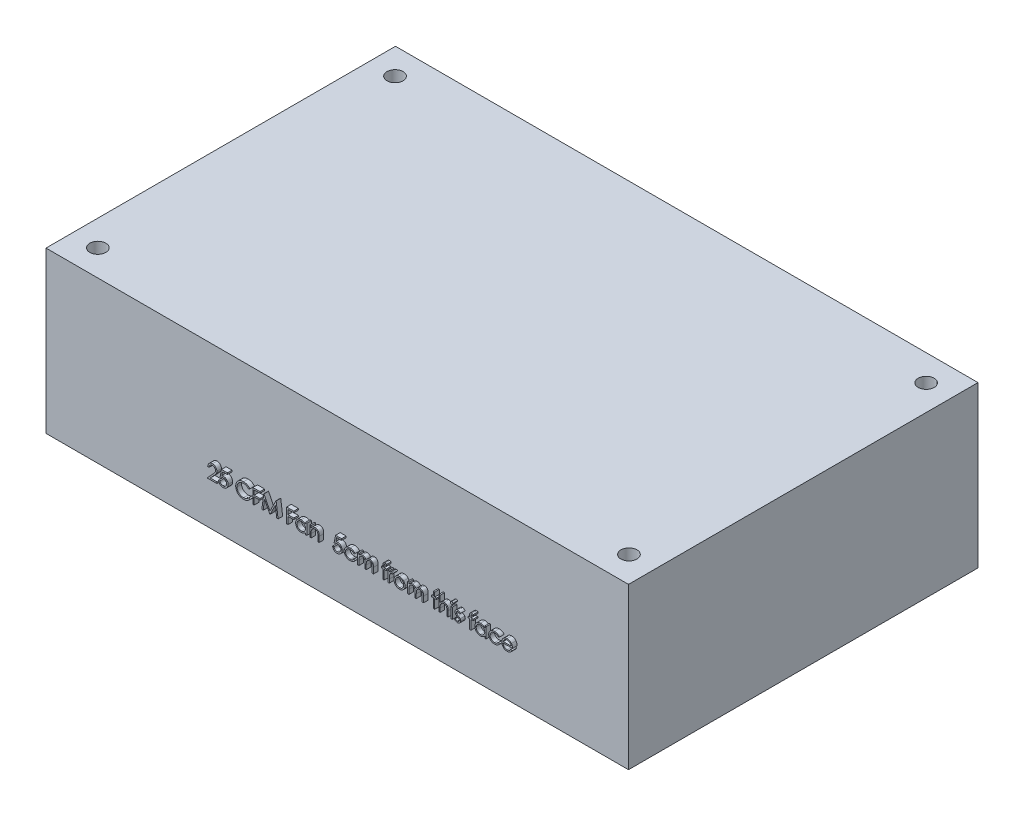
SolidWorks part; units mm, degrees
material "PA Type 6"
ref_plane "Front Plane" through (0, 0, 0) normal (0, 0, 1) x (1, 0, 0)
ref_plane "Top Plane" through (0, 0, 0) normal (0, 1, 0) x (1, 0, 0)
ref_plane "Right Plane" through (0, 0, 0) normal (1, 0, 0) x (0, 0, -1)
sketch "Sketch1" plane through (0, 0, 0) normal (0, 1, 0) x (1, 0, 0)
  line L0 (-57.9, 0) -> (57.9, 0) construction
  line L1 (-63.5, 38.1) -> (63.5, 38.1)
  line L2 (-63.5, 38.1) -> (-63.5, -38.1)
  line L3 (-63.5, -38.1) -> (63.5, -38.1)
  line L4 (63.5, 38.1) -> (63.5, -38.1)
  line L5 (-63.5, 38.1) -> (63.5, -38.1) construction
  line L6 (-63.5, -38.1) -> (63.5, 38.1) construction
  line L7 (-57.9, 32.4) -> (57.9, 32.4) construction
  line L8 (-57.9, 32.4) -> (-57.9, -32.4) construction
  line L9 (-57.9, -32.4) -> (57.9, -32.4) construction
  line L10 (57.9, 32.4) -> (57.9, -32.4) construction
  circle A0 centre (-57.9, 32.4) radius 1.75
  circle A1 centre (57.9, 32.4) radius 1.75
  circle A2 centre (57.9, -32.4) radius 1.75
  circle A3 centre (-57.9, -32.4) radius 1.75
  point P0 (0, 0)
  point P12 (0, 0)
  dimension "D6" = 3.5
  dimension "D1" = 127
  dimension "D2" = 76.2
  dimension "D3" = 115.8
  dimension "D4" = 64.8
  dimension "D5" = 5.7
extrude "Boss-Extrude1" add sketch "Sketch1" along normal blind 35
sketch "Sketch2" plane through (0, 0, 0) normal (0, -1, 0) x (1, 0, 0)
  circle A0 centre (0, 0) radius 14.424
  dimension "D1" = 28.848
extrude "Boss-Extrude2" add sketch "Sketch2" along normal blind 3
sketch "Sketch3" plane through (0, 0, 38.1) normal (0, 0, 1) x (1, 0, 0)
  line L0 (-26.9606, 12.3644) -> (-27.2455, 12.3644)
  line L1 (-25.8933, 11.3398) -> (-26.6877, 10.4919)
  line L2 (-26.6877, 10.4919) -> (-25.2102, 10.4919)
  line L3 (-25.2102, 10.4919) -> (-25.2102, 10.1663)
  line L4 (-25.2102, 10.1663) -> (-27.3676, 10.1663)
  line L5 (-27.3676, 10.1663) -> (-26.1363, 11.4803)
  line L6 (-22.9307, 13.3413) -> (-22.9307, 13.0157)
  line L7 (-22.9307, 13.0157) -> (-24.0107, 13.0157)
  line L8 (-24.0107, 13.0157) -> (-24.1818, 12.1806)
  line L9 (-24.8846, 10.9804) -> (-24.5997, 10.9804)
  line L10 (-24.5589, 11.7538) -> (-24.2333, 13.3413)
  line L11 (-24.2333, 13.3413) -> (-22.9307, 13.3413)
  line L12 (-18.0461, 12.7587) -> (-18.2954, 12.5679)
  line L13 (-18.2954, 10.9397) -> (-18.0461, 10.7508)
  line L14 (-17.3948, 13.3413) -> (-15.8481, 13.3413)
  line L15 (-15.8481, 13.3413) -> (-15.8481, 13.0157)
  line L16 (-15.8481, 13.0157) -> (-17.1099, 13.0157)
  line L17 (-17.1099, 13.0157) -> (-17.1099, 12.0387)
  line L18 (-17.1099, 12.0387) -> (-15.8481, 12.0387)
  line L19 (-15.8481, 12.0387) -> (-15.8481, 11.7131)
  line L20 (-15.8481, 11.7131) -> (-17.1099, 11.7131)
  line L21 (-17.1099, 11.7131) -> (-17.1099, 10.1663)
  line L22 (-17.1099, 10.1663) -> (-17.3948, 10.1663)
  line L23 (-17.3948, 10.1663) -> (-17.3948, 13.3413)
  line L24 (-15.441, 10.1663) -> (-15.0219, 13.3413)
  line L25 (-15.0219, 13.3413) -> (-14.9812, 13.3413)
  line L26 (-14.9812, 13.3413) -> (-13.6703, 10.7362)
  line L27 (-13.6703, 10.7362) -> (-12.3627, 13.3413)
  line L28 (-12.3627, 13.3413) -> (-12.3213, 13.3413)
  line L29 (-12.3213, 13.3413) -> (-11.8997, 10.1663)
  line L30 (-11.8997, 10.1663) -> (-12.1859, 10.1663)
  line L31 (-12.1859, 10.1663) -> (-12.4899, 12.4509)
  line L32 (-12.4899, 12.4509) -> (-13.636, 10.1663)
  line L33 (-13.636, 10.1663) -> (-13.7002, 10.1663)
  line L34 (-13.7002, 10.1663) -> (-14.8508, 12.456)
  line L35 (-14.8508, 12.456) -> (-15.1542, 10.1663)
  line L36 (-15.1542, 10.1663) -> (-15.441, 10.1663)
  line L37 (-10.0272, 13.3413) -> (-8.4804, 13.3413)
  line L38 (-8.4804, 13.3413) -> (-8.4804, 13.0157)
  line L39 (-8.4804, 13.0157) -> (-9.7423, 13.0157)
  line L40 (-9.7423, 13.0157) -> (-9.7423, 12.0387)
  line L41 (-9.7423, 12.0387) -> (-8.4804, 12.0387)
  line L42 (-8.4804, 12.0387) -> (-8.4804, 11.7131)
  line L43 (-8.4804, 11.7131) -> (-9.7423, 11.7131)
  line L44 (-9.7423, 11.7131) -> (-9.7423, 10.1663)
  line L45 (-9.7423, 10.1663) -> (-10.0272, 10.1663)
  line L46 (-10.0272, 10.1663) -> (-10.0272, 13.3413)
  line L47 (-5.6311, 12.4865) -> (-5.6311, 10.1663)
  line L48 (-5.6311, 10.1663) -> (-5.916, 10.1663)
  line L49 (-5.916, 10.1663) -> (-5.916, 10.5676)
  line L50 (-5.916, 12.0572) -> (-5.916, 12.4865)
  line L51 (-5.916, 12.4865) -> (-5.6311, 12.4865)
  line L52 (-4.9798, 12.4865) -> (-4.6948, 12.4865)
  line L53 (-4.6948, 12.4865) -> (-4.6948, 12.068)
  line L54 (-2.9445, 11.3512) -> (-2.9445, 10.1663)
  line L55 (-2.9445, 10.1663) -> (-3.2295, 10.1663)
  line L56 (-3.2295, 10.1663) -> (-3.2295, 11.2577)
  line L57 (-4.6948, 11.0052) -> (-4.6948, 10.1663)
  line L58 (-4.6948, 10.1663) -> (-4.9798, 10.1663)
  line L59 (-4.9798, 10.1663) -> (-4.9798, 12.4865)
  line L60 (1.9401, 13.3413) -> (1.9401, 13.0157)
  line L61 (1.9401, 13.0157) -> (0.8601, 13.0157)
  line L62 (0.8601, 13.0157) -> (0.689, 12.1806)
  line L63 (-0.0138, 10.9804) -> (0.2712, 10.9804)
  line L64 (0.3119, 11.7538) -> (0.6375, 13.3413)
  line L65 (0.6375, 13.3413) -> (1.9401, 13.3413)
  line L66 (4.8709, 11.9834) -> (4.6324, 11.8352)
  line L67 (4.6324, 10.8176) -> (4.8709, 10.6611)
  line L68 (5.4407, 12.4865) -> (5.7257, 12.4865)
  line L69 (5.7257, 12.4865) -> (5.7257, 12.0833)
  line L70 (8.9007, 11.4231) -> (8.9007, 10.1663)
  line L71 (8.9007, 10.1663) -> (8.6157, 10.1663)
  line L72 (8.6157, 10.1663) -> (8.6157, 11.4244)
  line L73 (7.3132, 11.0688) -> (7.3132, 10.1663)
  line L74 (7.3132, 10.1663) -> (7.0282, 10.1663)
  line L75 (7.0282, 10.1663) -> (7.0282, 11.3461)
  line L76 (5.7257, 11.1426) -> (5.7257, 10.1663)
  line L77 (5.7257, 10.1663) -> (5.4407, 10.1663)
  line L78 (5.4407, 10.1663) -> (5.4407, 12.4865)
  line L79 (11.75, 13.4036) -> (11.75, 13.1073)
  line L80 (11.2228, 12.8083) -> (11.2228, 12.4865)
  line L81 (11.2228, 12.4865) -> (11.7093, 12.4865)
  line L82 (11.7093, 12.4865) -> (11.7093, 12.2016)
  line L83 (11.7093, 12.2016) -> (11.2221, 12.2016)
  line L84 (11.2221, 12.2016) -> (11.2209, 10.1663)
  line L85 (11.2209, 10.1663) -> (10.9359, 10.1663)
  line L86 (10.9359, 10.1663) -> (10.9359, 12.2016)
  line L87 (10.9359, 12.2016) -> (10.6103, 12.2016)
  line L88 (10.6103, 12.2016) -> (10.6103, 12.4865)
  line L89 (10.6103, 12.4865) -> (10.9359, 12.4865)
  line L90 (10.9359, 12.4865) -> (10.9359, 12.8573)
  line L91 (12.0757, 12.4865) -> (12.3606, 12.4865)
  line L92 (12.3606, 12.4865) -> (12.3606, 12.145)
  line L93 (13.1747, 12.4477) -> (13.0182, 12.2009)
  line L94 (12.3606, 10.9461) -> (12.3606, 10.1663)
  line L95 (12.3606, 10.1663) -> (12.0757, 10.1663)
  line L96 (12.0757, 10.1663) -> (12.0757, 12.4865)
  line L97 (16.3497, 12.4865) -> (16.6346, 12.4865)
  line L98 (16.6346, 12.4865) -> (16.6346, 12.0833)
  line L99 (19.8096, 11.4231) -> (19.8096, 10.1663)
  line L100 (19.8096, 10.1663) -> (19.5247, 10.1663)
  line L101 (19.5247, 10.1663) -> (19.5247, 11.4244)
  line L102 (18.2221, 11.0688) -> (18.2221, 10.1663)
  line L103 (18.2221, 10.1663) -> (17.9372, 10.1663)
  line L104 (17.9372, 10.1663) -> (17.9372, 11.3461)
  line L105 (16.6346, 11.1426) -> (16.6346, 10.1663)
  line L106 (16.6346, 10.1663) -> (16.3497, 10.1663)
  line L107 (16.3497, 10.1663) -> (16.3497, 12.4865)
  line L108 (21.967, 13.4227) -> (22.2519, 13.4227)
  line L109 (22.2519, 13.4227) -> (22.2519, 12.4865)
  line L110 (22.2519, 12.4865) -> (22.659, 12.4865)
  line L111 (22.659, 12.4865) -> (22.659, 12.2016)
  line L112 (22.659, 12.2016) -> (22.2519, 12.2016)
  line L113 (22.2519, 12.2016) -> (22.2519, 10.1663)
  line L114 (22.2519, 10.1663) -> (21.967, 10.1663)
  line L115 (21.967, 10.1663) -> (21.967, 12.2016)
  line L116 (21.967, 12.2016) -> (21.56, 12.2016)
  line L117 (21.56, 12.2016) -> (21.56, 12.4865)
  line L118 (21.56, 12.4865) -> (21.967, 12.4865)
  line L119 (21.967, 12.4865) -> (21.967, 13.4227)
  line L120 (23.1475, 13.4227) -> (23.4324, 13.4227)
  line L121 (23.4324, 13.4227) -> (23.4324, 12.0483)
  line L122 (25.1827, 11.3512) -> (25.1827, 10.1663)
  line L123 (25.1827, 10.1663) -> (24.8978, 10.1663)
  line L124 (24.8978, 10.1663) -> (24.8978, 11.2577)
  line L125 (23.4324, 11.0052) -> (23.4324, 10.1663)
  line L126 (23.4324, 10.1663) -> (23.1475, 10.1663)
  line L127 (23.1475, 10.1663) -> (23.1475, 13.4227)
  line L128 (25.7933, 12.4865) -> (26.0782, 12.4865)
  line L129 (26.0782, 12.4865) -> (26.0782, 10.1663)
  line L130 (26.0782, 10.1663) -> (25.7933, 10.1663)
  line L131 (25.7933, 10.1663) -> (25.7933, 12.4865)
  line L132 (27.8693, 12.1971) -> (27.6759, 11.998)
  line L133 (26.5667, 10.4398) -> (26.7556, 10.6548)
  line L134 (30.6779, 13.4036) -> (30.6779, 13.1073)
  line L135 (30.1507, 12.8083) -> (30.1507, 12.4865)
  line L136 (30.1507, 12.4865) -> (30.6372, 12.4865)
  line L137 (30.6372, 12.4865) -> (30.6372, 12.2016)
  line L138 (30.6372, 12.2016) -> (30.15, 12.2016)
  line L139 (30.15, 12.2016) -> (30.1487, 10.1663)
  line L140 (30.1487, 10.1663) -> (29.8638, 10.1663)
  line L141 (29.8638, 10.1663) -> (29.8638, 12.2016)
  line L142 (29.8638, 12.2016) -> (29.5382, 12.2016)
  line L143 (29.5382, 12.2016) -> (29.5382, 12.4865)
  line L144 (29.5382, 12.4865) -> (29.8638, 12.4865)
  line L145 (29.8638, 12.4865) -> (29.8638, 12.8573)
  line L146 (33.4459, 12.4865) -> (33.4459, 10.1663)
  line L147 (33.4459, 10.1663) -> (33.1609, 10.1663)
  line L148 (33.1609, 10.1663) -> (33.1609, 10.5676)
  line L149 (33.1609, 12.0572) -> (33.1609, 12.4865)
  line L150 (33.1609, 12.4865) -> (33.4459, 12.4865)
  line L151 (36.3766, 11.9834) -> (36.1381, 11.8352)
  line L152 (36.1381, 10.8176) -> (36.3766, 10.6611)
  line L153 (38.8507, 10.899) -> (39.1039, 10.7661)
  line L154 (39.226, 11.2653) -> (37.15, 11.2653)
  line L155 (37.1799, 11.5503) -> (38.9411, 11.5503)
  spline S0 degree 3 poles (-27.2455, 12.3644) (-27.2437, 12.4387) (-27.2318, 12.5478) (-27.1984, 12.6881) (-27.1639, 12.786) (-27.121, 12.8791) (-27.0695, 12.9671) (-27.0086, 13.0496) (-26.9394, 13.126) (-26.8644, 13.196) (-26.7834, 13.2564) (-26.6982, 13.3075) (-26.6092, 13.3502) (-26.5154, 13.3823) (-26.383, 13.4146) (-26.2797, 13.4229) (-26.2101, 13.4227) knots 0 0 0 0 0.135103 0.198979 0.261904 0.323495 0.385195 0.446969 0.509765 0.572251 0.633405 0.693251 0.752583 0.812579 0.873275 1 1 1 1
  spline S1 degree 3 poles (-26.2101, 13.4227) (-26.1417, 13.4228) (-26.041, 13.4144) (-25.9119, 13.385) (-25.8219, 13.3548) (-25.7375, 13.3142) (-25.6582, 13.2654) (-25.583, 13.2089) (-25.5153, 13.1425) (-25.4532, 13.0715) (-25.3996, 12.9958) (-25.3537, 12.9176) (-25.3154, 12.8363) (-25.2872, 12.7511) (-25.2583, 12.6328) (-25.2517, 12.5405) (-25.2509, 12.4789) knots 0 0 0 0 0.136517 0.200789 0.26383 0.325735 0.387291 0.449509 0.512968 0.576275 0.63758 0.697903 0.757172 0.816599 0.876653 1 1 1 1
  spline S2 degree 3 poles (-25.2509, 12.4789) (-25.2506, 12.3912) (-25.2675, 12.2602) (-25.3223, 12.0933) (-25.3712, 11.9929) (-25.4206, 11.9119) (-25.4652, 11.8453) (-25.5173, 11.7735) (-25.5778, 11.6969) (-25.6454, 11.6148) (-25.7498, 11.4935) (-25.8347, 11.4027) (-25.8933, 11.3398) knots 0 0 0 0 0.195672 0.292422 0.391343 0.444462 0.504229 0.570352 0.642546 0.722288 0.807921 1 1 1 1
  spline S3 degree 3 poles (-26.1363, 11.4803) (-26.0785, 11.5403) (-25.9962, 11.6272) (-25.8941, 11.7409) (-25.8288, 11.8158) (-25.7727, 11.8853) (-25.7229, 11.9472) (-25.683, 12.0041) (-25.6397, 12.0701) (-25.5979, 12.1507) (-25.5497, 12.2815) (-25.5358, 12.385) (-25.5359, 12.4534) knots 0 0 0 0 0.212829 0.306101 0.390647 0.466924 0.534481 0.593587 0.644557 0.7362 0.825024 1 1 1 1
  spline S4 degree 3 poles (-25.5359, 12.4534) (-25.5356, 12.4961) (-25.5422, 12.5594) (-25.5628, 12.6408) (-25.5845, 12.6991) (-25.6132, 12.7549) (-25.6481, 12.8081) (-25.6883, 12.8595) (-25.7349, 12.9077) (-25.7861, 12.9519) (-25.8402, 12.991) (-25.8974, 13.0237) (-25.9574, 13.0505) (-26.0203, 13.0715) (-26.1092, 13.0913) (-26.178, 13.0969) (-26.2247, 13.0971) knots 0 0 0 0 0.122122 0.180988 0.239933 0.299906 0.359989 0.421776 0.486576 0.551535 0.615018 0.677259 0.73973 0.80305 0.866495 1 1 1 1
  spline S5 degree 3 poles (-26.2247, 13.0971) (-26.2734, 13.0966) (-26.3456, 13.0918) (-26.4382, 13.0709) (-26.5033, 13.0499) (-26.5655, 13.0231) (-26.6243, 12.9898) (-26.6797, 12.9501) (-26.7318, 12.9051) (-26.7797, 12.855) (-26.8219, 12.7991) (-26.8587, 12.7384) (-26.8908, 12.6733) (-26.9169, 12.6029) (-26.9442, 12.5002) (-26.9566, 12.4196) (-26.9606, 12.3644) knots 0 0 0 0 0.126547 0.186887 0.245878 0.304041 0.362191 0.420976 0.48066 0.5406 0.600689 0.661936 0.724443 0.789038 0.856314 1 1 1 1
  spline S6 degree 3 poles (-24.1818, 12.1806) (-24.1169, 12.199) (-23.9937, 12.2307) (-23.867, 12.242) (-23.8078, 12.2423) knots 0 0 0 0 0.532901 1 1 1 1
  spline S7 degree 3 poles (-23.8078, 12.2423) (-23.7381, 12.2426) (-23.6352, 12.2338) (-23.5033, 12.2027) (-23.4108, 12.1708) (-23.3229, 12.1301) (-23.2405, 12.0792) (-23.1623, 12.0198) (-23.0898, 11.9514) (-23.024, 11.8762) (-22.9662, 11.7953) (-22.917, 11.7096) (-22.8775, 11.6181) (-22.846, 11.522) (-22.8173, 11.3838) (-22.8083, 11.2765) (-22.8086, 11.2037) knots 0 0 0 0 0.129394 0.190894 0.251281 0.310815 0.370371 0.430768 0.492881 0.555104 0.616067 0.677256 0.73826 0.800762 0.864778 1 1 1 1
  spline S8 degree 3 poles (-22.8086, 11.2037) (-22.8095, 11.1523) (-22.8125, 11.0756) (-22.8283, 10.9753) (-22.844, 10.9022) (-22.8645, 10.8309) (-22.8892, 10.761) (-22.9195, 10.6932) (-22.9527, 10.6267) (-22.9902, 10.563) (-23.0317, 10.5034) (-23.0756, 10.4471) (-23.1228, 10.3946) (-23.1738, 10.3463) (-23.2279, 10.3019) (-23.2848, 10.2607) (-23.3452, 10.2242) (-23.4079, 10.1907) (-23.4738, 10.1632) (-23.5414, 10.1386) (-23.6116, 10.119) (-23.6842, 10.1037) (-23.7857, 10.0895) (-23.8634, 10.0841) (-23.9159, 10.0849) knots 0 0 0 0 0.087434 0.130118 0.172554 0.214555 0.256298 0.298438 0.340849 0.382715 0.423924 0.464246 0.504074 0.543862 0.583567 0.623094 0.663229 0.703551 0.743938 0.784541 0.82575 0.867757 0.910745 1 1 1 1
  spline S9 degree 3 poles (-23.9159, 10.0849) (-23.9782, 10.0842) (-24.07, 10.093) (-24.1887, 10.1182) (-24.2723, 10.1459) (-24.3525, 10.1807) (-24.4281, 10.2248) (-24.5013, 10.2746) (-24.5689, 10.3335) (-24.6316, 10.3978) (-24.6878, 10.4676) (-24.7378, 10.5418) (-24.7808, 10.6206) (-24.8176, 10.7039) (-24.8567, 10.8231) (-24.8761, 10.9166) (-24.8846, 10.9804) knots 0 0 0 0 0.128708 0.190236 0.250724 0.310637 0.370766 0.431615 0.493523 0.555883 0.617342 0.678668 0.740711 0.802985 0.866803 1 1 1 1
  spline S10 degree 3 poles (-24.5997, 10.9804) (-24.5875, 10.9221) (-24.5635, 10.838) (-24.5134, 10.7373) (-24.4704, 10.6724) (-24.4191, 10.6158) (-24.3606, 10.5653) (-24.295, 10.5198) (-24.222, 10.4819) (-24.1451, 10.4496) (-24.0377, 10.4206) (-23.9549, 10.4097) (-23.8994, 10.4105) knots 0 0 0 0 0.181994 0.264377 0.34218 0.418618 0.496509 0.577369 0.661511 0.746733 0.831258 1 1 1 1
  spline S11 degree 3 poles (-23.8994, 10.4105) (-23.8459, 10.4106) (-23.7665, 10.4178) (-23.6639, 10.4414) (-23.5914, 10.4674) (-23.521, 10.499) (-23.4546, 10.5396) (-23.3903, 10.5863) (-23.3301, 10.6398) (-23.2749, 10.6987) (-23.2261, 10.7617) (-23.1855, 10.829) (-23.1512, 10.8992) (-23.1253, 10.9733) (-23.1001, 11.0784) (-23.094, 11.1604) (-23.0936, 11.2157) knots 0 0 0 0 0.126425 0.18768 0.248216 0.308305 0.369661 0.431699 0.495947 0.559758 0.622295 0.683911 0.745092 0.80674 0.869087 1 1 1 1
  spline S12 degree 3 poles (-23.0936, 11.2157) (-23.0938, 11.2655) (-23.0988, 11.3392) (-23.1215, 11.433) (-23.1446, 11.4984) (-23.1738, 11.5603) (-23.2096, 11.6187) (-23.2526, 11.6729) (-23.3017, 11.7229) (-23.3554, 11.769) (-23.4148, 11.8083) (-23.4785, 11.8414) (-23.5458, 11.87) (-23.6184, 11.8905) (-23.7226, 11.9115) (-23.8041, 11.9162) (-23.8593, 11.9166) knots 0 0 0 0 0.127916 0.18836 0.247216 0.30563 0.36377 0.422661 0.482687 0.5433 0.604118 0.664965 0.727413 0.791468 0.858055 1 1 1 1
  spline S13 degree 3 poles (-23.8593, 11.9166) (-23.9102, 11.9165) (-23.9884, 11.9109) (-24.0946, 11.8941) (-24.1802, 11.8763) (-24.2696, 11.8531) (-24.3973, 11.8149) (-24.4937, 11.7793) (-24.5589, 11.7538) knots 0 0 0 0 0.211023 0.3251 0.446502 0.573788 0.708901 1 1 1 1
  spline S14 degree 3 poles (-18.2954, 12.5679) (-18.3301, 12.6105) (-18.3851, 12.6715) (-18.4647, 12.7457) (-18.5263, 12.7977) (-18.5914, 12.8443) (-18.6584, 12.8881) (-18.7284, 12.9273) (-18.8252, 12.9749) (-18.9519, 13.0245) (-19.1673, 13.0811) (-19.3356, 13.0976) (-19.4492, 13.0971) knots 0 0 0 0 0.125475 0.187121 0.248294 0.309295 0.36985 0.430973 0.492456 0.616148 0.740844 1 1 1 1
  spline S15 degree 3 poles (-19.4492, 13.0971) (-19.5126, 13.0979) (-19.6069, 13.0911) (-19.7307, 13.0728) (-19.8211, 13.0528) (-19.9096, 13.0274) (-19.9968, 12.9971) (-20.0814, 12.9595) (-20.1645, 12.9181) (-20.2441, 12.8713) (-20.3194, 12.8202) (-20.3902, 12.7654) (-20.4565, 12.7068) (-20.5183, 12.6445) (-20.5753, 12.5779) (-20.6272, 12.5073) (-20.675, 12.4335) (-20.7178, 12.3569) (-20.7537, 12.277) (-20.7854, 12.1952) (-20.8106, 12.1107) (-20.8304, 12.0241) (-20.8491, 11.9042) (-20.8556, 11.8125) (-20.8548, 11.7506) knots 0 0 0 0 0.087502 0.130463 0.172752 0.215403 0.25765 0.300153 0.343121 0.385925 0.427686 0.468818 0.509492 0.549883 0.58998 0.630405 0.670869 0.711384 0.751627 0.791776 0.832459 0.873319 0.914543 1 1 1 1
  spline S16 degree 3 poles (-20.8548, 11.7506) (-20.8552, 11.6585) (-20.8424, 11.5223) (-20.801, 11.3473) (-20.7555, 11.2245) (-20.6993, 11.1067) (-20.6283, 10.9958) (-20.5461, 10.8902) (-20.4515, 10.7923) (-20.3477, 10.703) (-20.2364, 10.6243) (-20.1177, 10.5587) (-19.9931, 10.5041) (-19.8616, 10.4622) (-19.6741, 10.4219) (-19.5283, 10.4097) (-19.4295, 10.4105) knots 0 0 0 0 0.12629 0.186726 0.246146 0.305576 0.365429 0.426326 0.48884 0.551725 0.613919 0.675484 0.737334 0.800229 0.864502 1 1 1 1
  spline S17 degree 3 poles (-19.4295, 10.4105) (-19.3205, 10.4105) (-19.1585, 10.4259) (-18.9518, 10.4821) (-18.8055, 10.54) (-18.6664, 10.6154) (-18.4872, 10.739) (-18.3687, 10.8555) (-18.2954, 10.9397) knots 0 0 0 0 0.252949 0.374755 0.49594 0.617181 0.740909 1 1 1 1
  spline S18 degree 3 poles (-18.0461, 10.7508) (-18.0854, 10.6986) (-18.1478, 10.6236) (-18.2393, 10.532) (-18.3116, 10.4683) (-18.387, 10.4083) (-18.4669, 10.3536) (-18.5502, 10.3035) (-18.6367, 10.2575) (-18.7263, 10.2168) (-18.8188, 10.1819) (-18.9139, 10.1519) (-19.0116, 10.1271) (-19.112, 10.1079) (-19.2507, 10.0903) (-19.3564, 10.0844) (-19.4276, 10.0849) knots 0 0 0 0 0.123053 0.183475 0.243727 0.304279 0.364863 0.425946 0.487391 0.54922 0.611144 0.673529 0.736961 0.800785 0.866013 1 1 1 1
  spline S19 degree 3 poles (-19.4276, 10.0849) (-19.4951, 10.0841) (-19.595, 10.0895) (-19.726, 10.1036) (-19.8201, 10.1192) (-19.9119, 10.1377) (-20.0004, 10.1624) (-20.0865, 10.1902) (-20.1699, 10.2227) (-20.2507, 10.2595) (-20.3286, 10.301) (-20.4036, 10.347) (-20.4763, 10.3964) (-20.5458, 10.4508) (-20.6355, 10.5294) (-20.698, 10.5942) (-20.7371, 10.6401) knots 0 0 0 0 0.13775 0.203917 0.26878 0.332414 0.394754 0.45618 0.516996 0.577396 0.637198 0.696999 0.756756 0.816554 0.876948 1 1 1 1
  spline S20 degree 3 poles (-20.7371, 10.6401) (-20.8029, 10.717) (-20.8913, 10.8402) (-20.9849, 11.0183) (-21.0415, 11.1575) (-21.0857, 11.3026) (-21.1274, 11.5071) (-21.14, 11.6654) (-21.1397, 11.7723) knots 0 0 0 0 0.247156 0.36878 0.490734 0.613614 0.738958 1 1 1 1
  spline S21 degree 3 poles (-21.1397, 11.7723) (-21.1398, 11.8846) (-21.1255, 12.051) (-21.074, 12.2646) (-21.0201, 12.4154) (-20.9518, 12.5597) (-20.8674, 12.6966) (-20.7679, 12.8267) (-20.6542, 12.9483) (-20.5294, 13.0595) (-20.3957, 13.1573) (-20.2535, 13.2387) (-20.1043, 13.3067) (-19.9469, 13.3589) (-19.7232, 13.4088) (-19.5491, 13.4225) (-19.4314, 13.4227) knots 0 0 0 0 0.127014 0.187955 0.248014 0.307748 0.368235 0.42947 0.492743 0.556258 0.618217 0.679655 0.741246 0.803415 0.866815 1 1 1 1
  spline S22 degree 3 poles (-19.4314, 13.4227) (-19.3592, 13.4229) (-19.252, 13.418) (-19.1119, 13.3989) (-19.0106, 13.3797) (-18.9116, 13.356) (-18.8157, 13.325) (-18.7221, 13.2896) (-18.6316, 13.2488) (-18.5446, 13.203) (-18.4611, 13.1528) (-18.3818, 13.0981) (-18.306, 13.0394) (-18.2352, 12.9755) (-18.1443, 12.8856) (-18.0844, 12.8102) (-18.0461, 12.7587) knots 0 0 0 0 0.135683 0.201215 0.265682 0.329267 0.392395 0.45507 0.517127 0.57879 0.63974 0.700192 0.759806 0.819628 0.879355 1 1 1 1
  spline S23 degree 3 poles (-5.916, 10.5676) (-5.977, 10.4956) (-6.0754, 10.3953) (-6.2266, 10.2913) (-6.3433, 10.2294) (-6.4657, 10.1831) (-6.6381, 10.1382) (-6.7727, 10.1249) (-6.8637, 10.1256) knots 0 0 0 0 0.262085 0.38627 0.507165 0.6273 0.748145 1 1 1 1
  spline S24 degree 3 poles (-6.8637, 10.1256) (-6.9444, 10.1258) (-7.0644, 10.1362) (-7.2187, 10.1733) (-7.3287, 10.2113) (-7.4336, 10.2617) (-7.5344, 10.3221) (-7.6304, 10.3939) (-7.7203, 10.4761) (-7.8031, 10.5654) (-7.8757, 10.6606) (-7.9362, 10.7613) (-7.9869, 10.8663) (-8.0258, 10.9763) (-8.0627, 11.1312) (-8.0732, 11.2516) (-8.0734, 11.3328) knots 0 0 0 0 0.127433 0.189004 0.24993 0.310668 0.372329 0.434939 0.499576 0.564191 0.626735 0.688109 0.749294 0.810331 0.871901 1 1 1 1
  spline S25 degree 3 poles (-8.0734, 11.3328) (-8.0729, 11.4124) (-8.0632, 11.5309) (-8.0251, 11.6831) (-7.9856, 11.7913) (-7.9349, 11.8951) (-7.8733, 11.9943) (-7.8007, 12.0894) (-7.717, 12.178) (-7.6264, 12.2598) (-7.5294, 12.3309) (-7.4285, 12.3924) (-7.3221, 12.441) (-7.2119, 12.4804) (-7.0565, 12.5173) (-6.9359, 12.5265) (-6.8548, 12.5272) knots 0 0 0 0 0.126079 0.186904 0.247574 0.308003 0.369132 0.432033 0.496791 0.561611 0.624914 0.686726 0.748079 0.809582 0.871631 1 1 1 1
  spline S26 degree 3 poles (-6.8548, 12.5272) (-6.7621, 12.5269) (-6.6244, 12.515) (-6.4502, 12.4661) (-6.3281, 12.4172) (-6.2127, 12.3522) (-6.0659, 12.2405) (-5.9722, 12.1343) (-5.916, 12.0572) knots 0 0 0 0 0.254654 0.376015 0.495255 0.614798 0.738106 1 1 1 1
  spline S27 degree 3 poles (-6.8509, 12.2423) (-6.933, 12.2419) (-7.0558, 12.2283) (-7.211, 12.177) (-7.3207, 12.1251) (-7.4229, 12.0597) (-7.5143, 11.9807) (-7.5955, 11.8901) (-7.6638, 11.7884) (-7.7194, 11.6794) (-7.7719, 11.5278) (-7.7895, 11.4089) (-7.7884, 11.3296) knots 0 0 0 0 0.169593 0.252476 0.336244 0.419505 0.502036 0.584775 0.669846 0.754185 0.836658 1 1 1 1
  spline S28 degree 3 poles (-7.7884, 11.3296) (-7.7878, 11.2507) (-7.7727, 11.1314) (-7.7183, 10.9801) (-7.6628, 10.8701) (-7.5933, 10.768) (-7.5126, 10.6757) (-7.4201, 10.5963) (-7.3177, 10.5299) (-7.2083, 10.4763) (-7.0546, 10.4261) (-6.9341, 10.4102) (-6.8535, 10.4105) knots 0 0 0 0 0.162859 0.245484 0.330807 0.416493 0.499893 0.583048 0.667158 0.751312 0.833785 1 1 1 1
  spline S29 degree 3 poles (-6.8535, 10.4105) (-6.7716, 10.4109) (-6.6485, 10.4251) (-6.4917, 10.4759) (-6.3795, 10.5284) (-6.2749, 10.5935) (-6.181, 10.6697) (-6.1016, 10.7583) (-6.0343, 10.8557) (-5.9815, 10.9625) (-5.9293, 11.1162) (-5.9164, 11.2391) (-5.916, 11.3213) knots 0 0 0 0 0.168664 0.252552 0.33824 0.423103 0.505556 0.586176 0.667136 0.748499 0.830452 1 1 1 1
  spline S30 degree 3 poles (-5.916, 11.3213) (-5.9162, 11.3844) (-5.9242, 11.4779) (-5.9525, 11.5978) (-5.9818, 11.6825) (-6.0204, 11.7629) (-6.0669, 11.8396) (-6.1221, 11.912) (-6.1852, 11.9793) (-6.2543, 12.0406) (-6.3275, 12.0954) (-6.4054, 12.1403) (-6.487, 12.1776) (-6.5723, 12.2072) (-6.6935, 12.2341) (-6.7874, 12.2432) (-6.8509, 12.2423) knots 0 0 0 0 0.129188 0.191219 0.251913 0.312507 0.373494 0.435152 0.498741 0.562095 0.624187 0.685476 0.746097 0.807612 0.869967 1 1 1 1
  spline S31 degree 3 poles (-4.6948, 12.068) (-4.6374, 12.1426) (-4.5458, 12.2468) (-4.4031, 12.3562) (-4.2943, 12.4198) (-4.1803, 12.4677) (-4.0211, 12.5145) (-3.8959, 12.5268) (-3.8121, 12.5272) knots 0 0 0 0 0.273569 0.398988 0.51993 0.63811 0.756589 1 1 1 1
  spline S32 degree 3 poles (-3.8121, 12.5272) (-3.7283, 12.5267) (-3.6032, 12.513) (-3.4485, 12.4561) (-3.3427, 12.3988) (-3.2473, 12.3275) (-3.1635, 12.2444) (-3.0943, 12.1489) (-3.0478, 12.0602) (-3.0172, 11.9816) (-2.998, 11.9142) (-2.9816, 11.8392) (-2.9674, 11.7567) (-2.9579, 11.6662) (-2.9473, 11.5303) (-2.9438, 11.4244) (-2.9445, 11.3512) knots 0 0 0 0 0.151178 0.223488 0.295543 0.366976 0.437131 0.507044 0.57856 0.616614 0.658756 0.704491 0.754803 0.809332 0.868274 1 1 1 1
  spline S33 degree 3 poles (-3.2295, 11.2577) (-3.2299, 11.3181) (-3.23, 11.4047) (-3.2336, 11.5147) (-3.2372, 11.5849) (-3.2424, 11.6468) (-3.2491, 11.713) (-3.2568, 11.7583) (-3.2632, 11.7856) knots 0 0 0 0 0.34211 0.489826 0.623254 0.74008 0.841483 1 1 1 1
  spline S34 degree 3 poles (-3.2632, 11.7856) (-3.2791, 11.8553) (-3.3151, 11.9547) (-3.3951, 12.065) (-3.4657, 12.1305) (-3.5485, 12.1814) (-3.6795, 12.2306) (-3.7876, 12.2427) (-3.8617, 12.2423) knots 0 0 0 0 0.260833 0.378476 0.493178 0.609281 0.729981 1 1 1 1
  spline S35 degree 3 poles (-3.8617, 12.2423) (-3.907, 12.2425) (-3.9748, 12.2373) (-4.0625, 12.2184) (-4.1263, 12.1995) (-4.1876, 12.1735) (-4.2481, 12.1439) (-4.3058, 12.1072) (-4.3616, 12.0662) (-4.4136, 12.0207) (-4.462, 11.9728) (-4.5051, 11.9218) (-4.5442, 11.8684) (-4.5779, 11.812) (-4.6174, 11.7334) (-4.6395, 11.6707) (-4.651, 11.6279) knots 0 0 0 0 0.126627 0.188984 0.25023 0.312351 0.374574 0.438148 0.50292 0.567974 0.630771 0.692935 0.754398 0.815218 0.876117 1 1 1 1
  spline S36 degree 3 poles (-4.651, 11.6279) (-4.6594, 11.594) (-4.6689, 11.5382) (-4.6783, 11.4575) (-4.6847, 11.3842) (-4.6886, 11.3018) (-4.6946, 11.1747) (-4.6944, 11.0747) (-4.6948, 11.0052) knots 0 0 0 0 0.167615 0.271052 0.38946 0.520843 0.666399 1 1 1 1
  spline S37 degree 3 poles (0.689, 12.1806) (0.754, 12.199) (0.8771, 12.2307) (1.0038, 12.242) (1.063, 12.2423) knots 0 0 0 0 0.532901 1 1 1 1
  spline S38 degree 3 poles (1.063, 12.2423) (1.1327, 12.2426) (1.2356, 12.2338) (1.3676, 12.2027) (1.4601, 12.1708) (1.5479, 12.1301) (1.6303, 12.0792) (1.7085, 12.0198) (1.781, 11.9514) (1.8468, 11.8762) (1.9047, 11.7953) (1.9538, 11.7096) (1.9933, 11.6181) (2.0248, 11.522) (2.0535, 11.3838) (2.0625, 11.2765) (2.0622, 11.2037) knots 0 0 0 0 0.129394 0.190894 0.251281 0.310815 0.370371 0.430768 0.492881 0.555104 0.616067 0.677256 0.73826 0.800762 0.864778 1 1 1 1
  spline S39 degree 3 poles (2.0622, 11.2037) (2.0613, 11.1523) (2.0584, 11.0756) (2.0426, 10.9753) (2.0268, 10.9022) (2.0064, 10.8309) (1.9816, 10.761) (1.9513, 10.6932) (1.9181, 10.6267) (1.8807, 10.563) (1.8391, 10.5034) (1.7953, 10.4471) (1.7481, 10.3946) (1.6971, 10.3463) (1.6429, 10.3019) (1.5861, 10.2607) (1.5256, 10.2242) (1.4629, 10.1907) (1.397, 10.1632) (1.3295, 10.1386) (1.2593, 10.119) (1.1866, 10.1037) (1.0851, 10.0895) (1.0074, 10.0841) (0.9549, 10.0849) knots 0 0 0 0 0.087434 0.130118 0.172554 0.214555 0.256298 0.298438 0.340849 0.382715 0.423924 0.464246 0.504074 0.543862 0.583567 0.623094 0.663229 0.703551 0.743938 0.784541 0.82575 0.867757 0.910745 1 1 1 1
  spline S40 degree 3 poles (0.9549, 10.0849) (0.8926, 10.0842) (0.8008, 10.093) (0.6821, 10.1182) (0.5985, 10.1459) (0.5184, 10.1807) (0.4427, 10.2248) (0.3696, 10.2746) (0.302, 10.3335) (0.2392, 10.3978) (0.1831, 10.4676) (0.1331, 10.5418) (0.09, 10.6206) (0.0533, 10.7039) (0.0141, 10.8231) (-0.0052, 10.9166) (-0.0138, 10.9804) knots 0 0 0 0 0.128708 0.190236 0.250724 0.310637 0.370766 0.431615 0.493523 0.555883 0.617342 0.678668 0.740711 0.802985 0.866803 1 1 1 1
  spline S41 degree 3 poles (0.2712, 10.9804) (0.2834, 10.9221) (0.3073, 10.838) (0.3574, 10.7373) (0.4004, 10.6724) (0.4517, 10.6158) (0.5102, 10.5653) (0.5759, 10.5198) (0.6488, 10.4819) (0.7257, 10.4496) (0.8332, 10.4206) (0.9159, 10.4097) (0.9714, 10.4105) knots 0 0 0 0 0.181994 0.264377 0.34218 0.418618 0.496509 0.577369 0.661511 0.746733 0.831258 1 1 1 1
  spline S42 degree 3 poles (0.9714, 10.4105) (1.025, 10.4106) (1.1043, 10.4178) (1.2069, 10.4414) (1.2795, 10.4674) (1.3498, 10.499) (1.4162, 10.5396) (1.4805, 10.5863) (1.5408, 10.6398) (1.596, 10.6987) (1.6447, 10.7617) (1.6854, 10.829) (1.7196, 10.8992) (1.7456, 10.9733) (1.7708, 11.0784) (1.7769, 11.1604) (1.7773, 11.2157) knots 0 0 0 0 0.126425 0.18768 0.248216 0.308305 0.369661 0.431699 0.495947 0.559758 0.622295 0.683911 0.745092 0.80674 0.869087 1 1 1 1
  spline S43 degree 3 poles (1.7773, 11.2157) (1.777, 11.2655) (1.772, 11.3392) (1.7493, 11.433) (1.7263, 11.4984) (1.697, 11.5603) (1.6612, 11.6187) (1.6182, 11.6729) (1.5692, 11.7229) (1.5154, 11.769) (1.4561, 11.8083) (1.3923, 11.8414) (1.325, 11.87) (1.2524, 11.8905) (1.1482, 11.9115) (1.0667, 11.9162) (1.0115, 11.9166) knots 0 0 0 0 0.127916 0.18836 0.247216 0.30563 0.36377 0.422661 0.482687 0.5433 0.604118 0.664965 0.727413 0.791468 0.858055 1 1 1 1
  spline S44 degree 3 poles (1.0115, 11.9166) (0.9607, 11.9165) (0.8824, 11.9109) (0.7762, 11.8941) (0.6907, 11.8763) (0.6012, 11.8531) (0.4735, 11.8149) (0.3771, 11.7793) (0.3119, 11.7538) knots 0 0 0 0 0.211023 0.3251 0.446502 0.573788 0.708901 1 1 1 1
  spline S45 degree 3 poles (4.6324, 11.8352) (4.5831, 11.9009) (4.499, 11.9895) (4.37, 12.0851) (4.2673, 12.143) (4.1572, 12.1876) (3.9981, 12.2308) (3.8726, 12.2424) (3.7877, 12.2423) knots 0 0 0 0 0.252584 0.373506 0.493364 0.614609 0.73847 1 1 1 1
  spline S46 degree 3 poles (3.7877, 12.2423) (3.7193, 12.2413) (3.6178, 12.2353) (3.4879, 12.2062) (3.3963, 12.1779) (3.3095, 12.14) (3.2272, 12.094) (3.1489, 12.0404) (3.0766, 11.9783) (3.0106, 11.9108) (2.9533, 11.8385) (2.9035, 11.7634) (2.8644, 11.6838) (2.8324, 11.6015) (2.8038, 11.4847) (2.7946, 11.3941) (2.7949, 11.3328) knots 0 0 0 0 0.136921 0.201969 0.265462 0.328248 0.390817 0.45355 0.517542 0.580738 0.641922 0.701597 0.760313 0.818757 0.877718 1 1 1 1
  spline S47 degree 3 poles (2.7949, 11.3328) (2.7951, 11.2522) (2.8109, 11.1307) (2.866, 10.9772) (2.9223, 10.8669) (2.9935, 10.7647) (3.0771, 10.6731) (3.1732, 10.5938) (3.2809, 10.5281) (3.3977, 10.4753) (3.5663, 10.4241) (3.6998, 10.4109) (3.7896, 10.4105) knots 0 0 0 0 0.159965 0.240321 0.322529 0.405024 0.486597 0.567865 0.651333 0.736238 0.821529 1 1 1 1
  spline S48 degree 3 poles (3.7896, 10.4105) (3.8722, 10.4106) (3.9945, 10.4221) (4.1501, 10.4656) (4.2593, 10.5101) (4.3625, 10.5678) (4.4936, 10.6639) (4.5804, 10.7522) (4.6324, 10.8176) knots 0 0 0 0 0.255447 0.377298 0.498442 0.619372 0.741857 1 1 1 1
  spline S49 degree 3 poles (4.8709, 10.6611) (4.8433, 10.6192) (4.7985, 10.5588) (4.7304, 10.4857) (4.676, 10.4348) (4.6187, 10.3865) (4.5567, 10.3431) (4.492, 10.3022) (4.4237, 10.2653) (4.3527, 10.2322) (4.2789, 10.2037) (4.2027, 10.1793) (4.124, 10.1598) (4.0427, 10.1443) (3.9297, 10.1303) (3.8434, 10.1247) (3.7852, 10.1256) knots 0 0 0 0 0.119069 0.178197 0.236957 0.295932 0.355856 0.416473 0.477742 0.539903 0.602538 0.665422 0.729765 0.794829 0.861827 1 1 1 1
  spline S50 degree 3 poles (3.7852, 10.1256) (3.697, 10.1247) (3.5669, 10.1358) (3.3995, 10.1717) (3.2819, 10.2094) (3.17, 10.2579) (3.064, 10.3172) (2.9641, 10.3878) (2.8715, 10.4683) (2.7864, 10.5556) (2.7134, 10.6498) (2.65, 10.7474) (2.5991, 10.8507) (2.5587, 10.9581) (2.5211, 11.1099) (2.5097, 11.2277) (2.51, 11.3073) knots 0 0 0 0 0.136335 0.201096 0.26445 0.327005 0.389391 0.451976 0.51567 0.578973 0.640167 0.69974 0.758685 0.81782 0.876984 1 1 1 1
  spline S51 degree 3 poles (2.51, 11.3073) (2.5092, 11.3619) (2.5161, 11.4429) (2.5321, 11.5497) (2.552, 11.6274) (2.5751, 11.7041) (2.6046, 11.779) (2.6392, 11.8525) (2.6784, 11.9242) (2.7226, 11.9931) (2.7714, 12.0582) (2.8232, 12.1203) (2.8802, 12.1772) (2.9401, 12.2312) (3.0046, 12.2809) (3.0733, 12.3263) (3.1451, 12.3685) (3.22, 12.406) (3.2977, 12.4383) (3.3775, 12.466) (3.4596, 12.4878) (3.5436, 12.5061) (3.66, 12.5218) (3.7488, 12.5275) (3.8087, 12.5272) knots 0 0 0 0 0.082136 0.122636 0.162831 0.203007 0.243526 0.284173 0.32541 0.366855 0.407551 0.448187 0.488683 0.529015 0.569843 0.61137 0.653238 0.695446 0.737751 0.780043 0.822807 0.865978 0.909595 1 1 1 1
  spline S52 degree 3 poles (3.8087, 12.5272) (3.8845, 12.5274) (3.9976, 12.518) (4.1457, 12.4895) (4.2529, 12.4581) (4.3552, 12.4201) (4.4509, 12.3775) (4.5378, 12.328) (4.6176, 12.2738) (4.6903, 12.2127) (4.7802, 12.12) (4.8376, 12.0404) (4.8709, 11.9834) knots 0 0 0 0 0.182081 0.27191 0.362049 0.450066 0.533976 0.613602 0.690198 0.765413 0.841437 1 1 1 1
  spline S53 degree 3 poles (5.7257, 12.0833) (5.7735, 12.1517) (5.87, 12.2722) (5.9879, 12.3721) (6.0475, 12.4095) knots 0 0 0 0 0.543395 1 1 1 1
  spline S54 degree 3 poles (6.0475, 12.4095) (6.1215, 12.4478) (6.2774, 12.5083) (6.4435, 12.5266) (6.5258, 12.5272) knots 0 0 0 0 0.503035 1 1 1 1
  spline S55 degree 3 poles (6.5258, 12.5272) (6.5812, 12.5265) (6.6643, 12.5195) (6.7711, 12.491) (6.8479, 12.4617) (6.9202, 12.4261) (6.9865, 12.3843) (7.046, 12.3374) (7.0988, 12.2833) (7.1462, 12.2204) (7.2076, 12.1172) (7.2428, 12.0291) (7.2642, 11.9669) knots 0 0 0 0 0.166532 0.248836 0.331246 0.412957 0.490494 0.566156 0.639987 0.716765 0.802144 1 1 1 1
  spline S56 degree 3 poles (7.2642, 11.9669) (7.2879, 12.0114) (7.3269, 12.0753) (7.3853, 12.1543) (7.4307, 12.2088) (7.4782, 12.2589) (7.5282, 12.305) (7.5802, 12.3472) (7.6526, 12.3965) (7.7468, 12.4488) (7.9051, 12.5097) (8.0314, 12.5274) (8.1152, 12.5272) knots 0 0 0 0 0.141226 0.209116 0.27484 0.339483 0.402476 0.464942 0.526833 0.647415 0.765562 1 1 1 1
  spline S57 degree 3 poles (8.1152, 12.5272) (8.1911, 12.5266) (8.3045, 12.5142) (8.4444, 12.4616) (8.5401, 12.4088) (8.6264, 12.3424) (8.7014, 12.2634) (8.7647, 12.1724) (8.8061, 12.0868) (8.8341, 12.0112) (8.8514, 11.9468) (8.8667, 11.8759) (8.8794, 11.7984) (8.8886, 11.7141) (8.8982, 11.5884) (8.901, 11.4905) (8.9007, 11.4231) knots 0 0 0 0 0.147965 0.218797 0.28947 0.359724 0.429708 0.500497 0.574429 0.613947 0.657155 0.703973 0.754939 0.809707 0.868833 1 1 1 1
  spline S58 degree 3 poles (8.6157, 11.4244) (8.6158, 11.4814) (8.6149, 11.5633) (8.6085, 11.6676) (8.6031, 11.7349) (8.5956, 11.795) (8.586, 11.8477) (8.5757, 11.8936) (8.5587, 11.9445) (8.5316, 12.0006) (8.4902, 12.0612) (8.438, 12.1139) (8.3778, 12.1596) (8.3093, 12.1968) (8.206, 12.2333) (8.1223, 12.2426) (8.0656, 12.2423) knots 0 0 0 0 0.150563 0.216151 0.27568 0.328707 0.375904 0.417302 0.452693 0.517265 0.581217 0.645322 0.712024 0.78013 0.850218 1 1 1 1
  spline S59 degree 3 poles (8.0656, 12.2423) (7.9943, 12.2435) (7.8882, 12.226) (7.7549, 12.1734) (7.6622, 12.1168) (7.5769, 12.0489) (7.5035, 11.9683) (7.4429, 11.877) (7.4018, 11.7925) (7.3759, 11.7166) (7.3587, 11.6503) (7.3454, 11.5749) (7.3329, 11.491) (7.3248, 11.3979) (7.3145, 11.2564) (7.3136, 11.1456) (7.3132, 11.0688) knots 0 0 0 0 0.134707 0.201865 0.270788 0.340024 0.408083 0.476813 0.547346 0.58564 0.628865 0.677153 0.730803 0.789807 0.854325 1 1 1 1
  spline S60 degree 3 poles (7.0282, 11.3461) (7.0283, 11.4101) (7.0274, 11.502) (7.021, 11.6188) (7.0156, 11.6939) (7.008, 11.7605) (6.9993, 11.819) (6.989, 11.869) (6.9719, 11.924) (6.9459, 11.9845) (6.904, 12.049) (6.8517, 12.1055) (6.7904, 12.1538) (6.7215, 12.1936) (6.6177, 12.2329) (6.533, 12.2418) (6.4762, 12.2423) knots 0 0 0 0 0.158779 0.227738 0.289946 0.345499 0.393896 0.436374 0.472122 0.536384 0.599078 0.661948 0.726311 0.791771 0.858647 1 1 1 1
  spline S61 degree 3 poles (6.4762, 12.2423) (6.4074, 12.2428) (6.304, 12.2263) (6.1745, 12.1741) (6.082, 12.1201) (5.997, 12.053) (5.9226, 11.9742) (5.8601, 11.8845) (5.8186, 11.8009) (5.7918, 11.7269) (5.7741, 11.664) (5.7588, 11.5942) (5.7474, 11.5172) (5.7365, 11.4335) (5.7291, 11.3078) (5.7248, 11.2101) (5.7257, 11.1426) knots 0 0 0 0 0.136871 0.206114 0.277538 0.349772 0.421251 0.492911 0.567027 0.606614 0.649704 0.697303 0.749086 0.804881 0.865485 1 1 1 1
  spline S62 degree 3 poles (11.75, 13.1073) (11.6992, 13.1285) (11.6051, 13.1628) (11.506, 13.1783) (11.4613, 13.1785) knots 0 0 0 0 0.553028 1 1 1 1
  spline S63 degree 3 poles (11.4613, 13.1785) (11.4339, 13.1774) (11.3935, 13.1754) (11.3443, 13.159) (11.3127, 13.1436) (11.2864, 13.1242) (11.2639, 13.1048) (11.2476, 13.0828) (11.2388, 13.0624) (11.2334, 13.0435) (11.2318, 13.0241) (11.2278, 13.0003) (11.2267, 12.9711) (11.2242, 12.9375) (11.2244, 12.8825) (11.2214, 12.8391) (11.2228, 12.8083) knots 0 0 0 0 0.158724 0.229424 0.297719 0.360776 0.416988 0.468546 0.516675 0.544534 0.581509 0.628334 0.683433 0.749506 0.822818 1 1 1 1
  spline S64 degree 3 poles (10.9359, 12.8573) (10.9352, 12.8968) (10.938, 12.9536) (10.9417, 13.0266) (10.9469, 13.0743) (10.953, 13.1177) (10.9616, 13.1561) (10.9698, 13.1907) (10.9846, 13.2298) (11.0068, 13.2741) (11.0426, 13.3209) (11.0856, 13.3629) (11.137, 13.3983) (11.1948, 13.4277) (11.283, 13.4567) (11.3544, 13.4626) (11.4028, 13.4634) knots 0 0 0 0 0.133856 0.192948 0.247916 0.296642 0.341504 0.38163 0.416905 0.483173 0.548917 0.616062 0.686302 0.759645 0.83539 1 1 1 1
  spline S65 degree 3 poles (11.4028, 13.4634) (11.4562, 13.4628) (11.574, 13.4519) (11.6882, 13.4211) (11.75, 13.4036) knots 0 0 0 0 0.453863 1 1 1 1
  spline S66 degree 3 poles (12.3606, 12.145) (12.3996, 12.2064) (12.4613, 12.2914) (12.5572, 12.3846) (12.6277, 12.4377) (12.7006, 12.4774) (12.7982, 12.5161) (12.8758, 12.5269) (12.9267, 12.5272) knots 0 0 0 0 0.306112 0.438367 0.560541 0.675317 0.786114 1 1 1 1
  spline S67 degree 3 poles (12.9267, 12.5272) (12.9675, 12.5269) (13.055, 12.5116) (13.1345, 12.4721) (13.1747, 12.4477) knots 0 0 0 0 0.463523 1 1 1 1
  spline S68 degree 3 poles (13.0182, 12.2009) (12.9923, 12.2124) (12.9456, 12.2335) (12.895, 12.242) (12.8726, 12.2423) knots 0 0 0 0 0.56023 1 1 1 1
  spline S69 degree 3 poles (12.8726, 12.2423) (12.8259, 12.2423) (12.7543, 12.2252) (12.6682, 12.1736) (12.6154, 12.1299) (12.5745, 12.0877) (12.5454, 12.0508) (12.5186, 12.0095) (12.4931, 11.9644) (12.4698, 11.9147) (12.44, 11.8412) (12.4223, 11.7827) (12.4115, 11.7424) knots 0 0 0 0 0.191338 0.295191 0.410312 0.47193 0.536425 0.603119 0.674118 0.749332 0.828283 1 1 1 1
  spline S70 degree 3 poles (12.4115, 11.7424) (12.4008, 11.7018) (12.3904, 11.6337) (12.3793, 11.5341) (12.3729, 11.4407) (12.3669, 11.3349) (12.3621, 11.1687) (12.3601, 11.0377) (12.3606, 10.9461) knots 0 0 0 0 0.156938 0.2586 0.375891 0.508166 0.656238 1 1 1 1
  spline S71 degree 3 poles (14.5803, 12.5272) (14.6657, 12.5281) (14.792, 12.5158) (14.9535, 12.4753) (15.0677, 12.4343) (15.175, 12.3792) (15.3133, 12.2907) (15.4054, 12.2066) (15.4618, 12.145) knots 0 0 0 0 0.258332 0.382134 0.503804 0.624693 0.746871 1 1 1 1
  spline S72 degree 3 poles (15.4618, 12.145) (15.5136, 12.0884) (15.5829, 11.9978) (15.6575, 11.8668) (15.702, 11.765) (15.7371, 11.6594) (15.7708, 11.5116) (15.7794, 11.3971) (15.7798, 11.32) knots 0 0 0 0 0.253834 0.376506 0.498534 0.621368 0.744565 1 1 1 1
  spline S73 degree 3 poles (15.7798, 11.32) (15.7803, 11.2424) (15.7697, 11.1271) (15.7346, 10.978) (15.6976, 10.8711) (15.6501, 10.7678) (15.5922, 10.6685) (15.5233, 10.5731) (15.4453, 10.4824) (15.3591, 10.3988) (15.2656, 10.3259) (15.1665, 10.2635) (15.0607, 10.2132) (14.9491, 10.1736) (14.7894, 10.1356) (14.6646, 10.1259) (14.5803, 10.1256) knots 0 0 0 0 0.123337 0.183265 0.243172 0.302898 0.363774 0.425605 0.489659 0.553785 0.616222 0.677854 0.739517 0.802097 0.865866 1 1 1 1
  spline S74 degree 3 poles (14.5803, 10.1256) (14.4956, 10.126) (14.3704, 10.1355) (14.2102, 10.1736) (14.0985, 10.2133) (13.9922, 10.2635) (13.8926, 10.3257) (13.799, 10.3988) (13.7127, 10.4824) (13.6347, 10.5731) (13.5659, 10.6685) (13.5079, 10.7678) (13.4604, 10.8711) (13.4234, 10.978) (13.3884, 11.1271) (13.3778, 11.2424) (13.3782, 11.32) knots 0 0 0 0 0.134635 0.198324 0.260825 0.322714 0.384555 0.446913 0.510958 0.574931 0.636685 0.697483 0.757134 0.816966 0.876818 1 1 1 1
  spline S75 degree 3 poles (13.3782, 11.32) (13.3787, 11.3969) (13.3873, 11.5112) (13.4209, 11.6586) (13.456, 11.7638) (13.501, 11.8651) (13.5746, 11.9964) (13.6451, 12.0863) (13.6962, 12.1431) knots 0 0 0 0 0.255238 0.378679 0.501088 0.622714 0.746241 1 1 1 1
  spline S76 degree 3 poles (13.6962, 12.1431) (13.7521, 12.2055) (13.8451, 12.2888) (13.983, 12.3791) (14.0916, 12.4331) (14.2056, 12.4755) (14.3679, 12.5158) (14.4945, 12.528) (14.5803, 12.5272) knots 0 0 0 0 0.252713 0.374819 0.496436 0.617911 0.741288 1 1 1 1
  spline S77 degree 3 poles (14.579, 12.2423) (14.5183, 12.2421) (14.428, 12.2339) (14.3119, 12.2057) (14.2289, 12.1761) (14.1494, 12.1379) (14.0733, 12.091) (14.0004, 12.036) (13.932, 11.973) (13.8692, 11.9042) (13.8144, 11.8308) (13.7677, 11.7542) (13.7288, 11.6741) (13.6999, 11.5899) (13.6714, 11.4718) (13.6633, 11.3799) (13.6632, 11.3181) knots 0 0 0 0 0.126044 0.187165 0.247399 0.30838 0.36978 0.432584 0.497641 0.562401 0.625557 0.687332 0.748313 0.809791 0.871768 1 1 1 1
  spline S78 degree 3 poles (13.6632, 11.3181) (13.6634, 11.2377) (13.6775, 11.1168) (13.7304, 10.9644) (13.7835, 10.8559) (13.8501, 10.7555) (13.9286, 10.666) (14.0181, 10.5887) (14.1175, 10.5246) (14.2249, 10.4737) (14.3776, 10.4248) (14.498, 10.4096) (14.579, 10.4105) knots 0 0 0 0 0.168179 0.251488 0.335841 0.419834 0.502345 0.583649 0.665931 0.748717 0.831047 1 1 1 1
  spline S79 degree 3 poles (14.579, 10.4105) (14.66, 10.4097) (14.7803, 10.4246) (14.9327, 10.4738) (15.04, 10.5245) (15.1393, 10.5889) (15.2295, 10.6655) (15.3073, 10.7557) (15.3738, 10.856) (15.4278, 10.9642) (15.4804, 11.1168) (15.4948, 11.2377) (15.4949, 11.3181) knots 0 0 0 0 0.168983 0.250908 0.333708 0.416005 0.49766 0.579893 0.663902 0.748466 0.831791 1 1 1 1
  spline S80 degree 3 poles (15.4949, 11.3181) (15.4947, 11.3799) (15.4867, 11.4718) (15.4582, 11.5899) (15.4292, 11.6741) (15.3905, 11.7544) (15.3429, 11.8306) (15.2883, 11.9044) (15.2248, 11.9728) (15.1565, 12.0361) (15.0835, 12.0911) (15.0075, 12.1377) (14.9282, 12.1765) (14.8452, 12.2054) (14.7295, 12.2341) (14.6395, 12.242) (14.579, 12.2423) knots 0 0 0 0 0.128274 0.19027 0.251768 0.312769 0.374793 0.43797 0.503047 0.568125 0.63095 0.692369 0.752973 0.813641 0.874355 1 1 1 1
  spline S81 degree 3 poles (16.6346, 12.0833) (16.6824, 12.1517) (16.7789, 12.2722) (16.8969, 12.3721) (16.9565, 12.4095) knots 0 0 0 0 0.543395 1 1 1 1
  spline S82 degree 3 poles (16.9565, 12.4095) (17.0305, 12.4478) (17.1863, 12.5083) (17.3525, 12.5266) (17.4348, 12.5272) knots 0 0 0 0 0.503035 1 1 1 1
  spline S83 degree 3 poles (17.4348, 12.5272) (17.4901, 12.5265) (17.5733, 12.5195) (17.6801, 12.491) (17.7569, 12.4617) (17.8292, 12.4261) (17.8955, 12.3843) (17.955, 12.3374) (18.0077, 12.2833) (18.0551, 12.2204) (18.1166, 12.1172) (18.1518, 12.0291) (18.1732, 11.9669) knots 0 0 0 0 0.166532 0.248836 0.331246 0.412957 0.490494 0.566156 0.639987 0.716765 0.802144 1 1 1 1
  spline S84 degree 3 poles (18.1732, 11.9669) (18.1969, 12.0114) (18.2359, 12.0753) (18.2943, 12.1543) (18.3396, 12.2088) (18.3872, 12.2589) (18.4371, 12.305) (18.4892, 12.3472) (18.5616, 12.3965) (18.6557, 12.4488) (18.8141, 12.5097) (18.9404, 12.5274) (19.0242, 12.5272) knots 0 0 0 0 0.141226 0.209116 0.27484 0.339483 0.402476 0.464942 0.526833 0.647415 0.765562 1 1 1 1
  spline S85 degree 3 poles (19.0242, 12.5272) (19.1001, 12.5266) (19.2135, 12.5142) (19.3534, 12.4616) (19.4491, 12.4088) (19.5354, 12.3424) (19.6104, 12.2634) (19.6737, 12.1724) (19.7151, 12.0868) (19.7431, 12.0112) (19.7604, 11.9468) (19.7757, 11.8759) (19.7884, 11.7984) (19.7976, 11.7141) (19.8072, 11.5884) (19.81, 11.4905) (19.8096, 11.4231) knots 0 0 0 0 0.147965 0.218797 0.28947 0.359724 0.429708 0.500497 0.574429 0.613947 0.657155 0.703973 0.754939 0.809707 0.868833 1 1 1 1
  spline S86 degree 3 poles (19.5247, 11.4244) (19.5248, 11.4814) (19.5239, 11.5633) (19.5174, 11.6676) (19.5121, 11.7349) (19.5046, 11.795) (19.4949, 11.8477) (19.4847, 11.8936) (19.4677, 11.9445) (19.4405, 12.0006) (19.3992, 12.0612) (19.347, 12.1139) (19.2868, 12.1596) (19.2183, 12.1968) (19.115, 12.2333) (19.0313, 12.2426) (18.9745, 12.2423) knots 0 0 0 0 0.150563 0.216151 0.27568 0.328707 0.375904 0.417302 0.452693 0.517265 0.581217 0.645322 0.712024 0.78013 0.850218 1 1 1 1
  spline S87 degree 3 poles (18.9745, 12.2423) (18.9033, 12.2435) (18.7972, 12.226) (18.6639, 12.1734) (18.5711, 12.1168) (18.4858, 12.0489) (18.4125, 11.9683) (18.3518, 11.877) (18.3108, 11.7925) (18.2848, 11.7166) (18.2677, 11.6503) (18.2544, 11.5749) (18.2419, 11.491) (18.2338, 11.3979) (18.2234, 11.2564) (18.2226, 11.1456) (18.2221, 11.0688) knots 0 0 0 0 0.134707 0.201865 0.270788 0.340024 0.408083 0.476813 0.547346 0.58564 0.628865 0.677153 0.730803 0.789807 0.854325 1 1 1 1
  spline S88 degree 3 poles (17.9372, 11.3461) (17.9373, 11.4101) (17.9364, 11.502) (17.9299, 11.6188) (17.9246, 11.6939) (17.9169, 11.7605) (17.9082, 11.819) (17.8979, 11.869) (17.8809, 11.924) (17.8548, 11.9845) (17.8129, 12.049) (17.7607, 12.1055) (17.6994, 12.1538) (17.6304, 12.1936) (17.5267, 12.2329) (17.442, 12.2418) (17.3851, 12.2423) knots 0 0 0 0 0.158779 0.227738 0.289946 0.345499 0.393896 0.436374 0.472122 0.536384 0.599078 0.661948 0.726311 0.791771 0.858647 1 1 1 1
  spline S89 degree 3 poles (17.3851, 12.2423) (17.3164, 12.2428) (17.213, 12.2263) (17.0835, 12.1741) (16.991, 12.1201) (16.906, 12.053) (16.8316, 11.9742) (16.7691, 11.8845) (16.7276, 11.8009) (16.7008, 11.7269) (16.683, 11.664) (16.6678, 11.5942) (16.6564, 11.5172) (16.6455, 11.4335) (16.638, 11.3078) (16.6337, 11.2101) (16.6346, 11.1426) knots 0 0 0 0 0.136871 0.206114 0.277538 0.349772 0.421251 0.492911 0.567027 0.606614 0.649704 0.697303 0.749086 0.804881 0.865485 1 1 1 1
  spline S90 degree 3 poles (23.4324, 12.0483) (23.4897, 12.1245) (23.5847, 12.2272) (23.7257, 12.3422) (23.8349, 12.4093) (23.9483, 12.4622) (24.1069, 12.5128) (24.2318, 12.527) (24.3152, 12.5272) knots 0 0 0 0 0.273996 0.400684 0.522555 0.641534 0.759969 1 1 1 1
  spline S91 degree 3 poles (24.3152, 12.5272) (24.399, 12.5266) (24.5241, 12.513) (24.6788, 12.4561) (24.7846, 12.3989) (24.8797, 12.3275) (24.9639, 12.2451) (25.0327, 12.1496) (25.0795, 12.0614) (25.11, 11.9829) (25.1293, 11.9155) (25.1456, 11.8405) (25.1599, 11.7578) (25.1693, 11.667) (25.18, 11.5308) (25.1834, 11.4246) (25.1827, 11.3512) knots 0 0 0 0 0.151155 0.223454 0.295497 0.36692 0.436794 0.506696 0.577864 0.615912 0.658048 0.703776 0.75408 0.808979 0.867913 1 1 1 1
  spline S92 degree 3 poles (24.8978, 11.2577) (24.8974, 11.3181) (24.8972, 11.4047) (24.8937, 11.5147) (24.8898, 11.5849) (24.8857, 11.6468) (24.8787, 11.713) (24.8712, 11.7583) (24.8647, 11.7856) knots 0 0 0 0 0.342141 0.489871 0.623312 0.740056 0.841468 1 1 1 1
  spline S93 degree 3 poles (24.8647, 11.7856) (24.8471, 11.8552) (24.8103, 11.9544) (24.7302, 12.0651) (24.6597, 12.1303) (24.5775, 12.1814) (24.4469, 12.2308) (24.339, 12.2426) (24.2649, 12.2423) knots 0 0 0 0 0.261954 0.379638 0.494379 0.609866 0.729887 1 1 1 1
  spline S94 degree 3 poles (24.2649, 12.2423) (24.2196, 12.2425) (24.1518, 12.2373) (24.0641, 12.2184) (24.0003, 12.1994) (23.9392, 12.1736) (23.879, 12.1438) (23.8215, 12.1072) (23.7656, 12.0662) (23.7136, 12.0207) (23.6652, 11.9728) (23.6221, 11.9218) (23.583, 11.8684) (23.5493, 11.812) (23.5099, 11.7334) (23.4877, 11.6707) (23.4763, 11.6279) knots 0 0 0 0 0.126694 0.189084 0.250363 0.312516 0.374243 0.43785 0.502657 0.567745 0.630576 0.692772 0.754268 0.815121 0.876051 1 1 1 1
  spline S95 degree 3 poles (23.4763, 11.6279) (23.4678, 11.5944) (23.4582, 11.539) (23.4489, 11.4588) (23.4425, 11.3854) (23.4386, 11.3029) (23.4327, 11.1753) (23.4328, 11.075) (23.4324, 11.0052) knots 0 0 0 0 0.165611 0.269045 0.387448 0.518827 0.665394 1 1 1 1
  spline S96 degree 3 poles (25.9345, 13.4634) (25.969, 13.4634) (26.021, 13.4555) (26.0825, 13.4239) (26.1229, 13.3927) (26.1576, 13.3559) (26.1902, 13.2986) (26.2005, 13.2503) (26.2003, 13.2179) knots 0 0 0 0 0.258284 0.384341 0.51198 0.638632 0.75923 1 1 1 1
  spline S97 degree 3 poles (26.2003, 13.2179) (26.2004, 13.1862) (26.1902, 13.1386) (26.1573, 13.0824) (26.1229, 13.0457) (26.0824, 13.0145) (26.021, 12.9829) (25.969, 12.975) (25.9345, 12.975) knots 0 0 0 0 0.237546 0.357497 0.484917 0.613329 0.74015 1 1 1 1
  spline S98 degree 3 poles (25.9345, 12.975) (25.9006, 12.9747) (25.8493, 12.9833) (25.7885, 13.0145) (25.7479, 13.0455) (25.7142, 13.0827) (25.6813, 13.1386) (25.6711, 13.1863) (25.6712, 13.2179) knots 0 0 0 0 0.256661 0.384213 0.513365 0.640443 0.761085 1 1 1 1
  spline S99 degree 3 poles (25.6712, 13.2179) (25.671, 13.2502) (25.6812, 13.2987) (25.714, 13.3556) (25.748, 13.3929) (25.7885, 13.4239) (25.8493, 13.4551) (25.9006, 13.4636) (25.9345, 13.4634) knots 0 0 0 0 0.242149 0.363437 0.489745 0.618115 0.744894 1 1 1 1
  spline S100 degree 3 poles (27.6759, 11.998) (27.6443, 12.0357) (27.5958, 12.0883) (27.5252, 12.1463) (27.4753, 12.1817) (27.425, 12.2084) (27.3596, 12.234) (27.3086, 12.2422) (27.2752, 12.2423) knots 0 0 0 0 0.305036 0.441309 0.565963 0.683525 0.793334 1 1 1 1
  spline S101 degree 3 poles (27.2752, 12.2423) (27.2356, 12.2431) (27.1766, 12.2303) (27.1064, 12.1908) (27.0609, 12.1491) (27.0224, 12.1013) (26.9846, 12.0297) (26.9739, 11.9698) (26.9737, 11.93) knots 0 0 0 0 0.245901 0.369166 0.498511 0.628504 0.751028 1 1 1 1
  spline S102 degree 3 poles (26.9737, 11.93) (26.9738, 11.8934) (26.988, 11.817) (27.0284, 11.7508) (27.0526, 11.7195) knots 0 0 0 0 0.479403 1 1 1 1
  spline S103 degree 3 poles (27.0526, 11.7195) (27.0671, 11.6998) (27.0954, 11.673) (27.1368, 11.6365) (27.176, 11.6075) (27.2203, 11.577) (27.29, 11.534) (27.3446, 11.5008) (27.384, 11.4803) knots 0 0 0 0 0.17756 0.283982 0.402217 0.533568 0.676121 1 1 1 1
  spline S104 degree 3 poles (27.384, 11.4803) (27.4318, 11.4539) (27.5006, 11.4141) (27.5856, 11.3571) (27.6414, 11.3166) (27.6903, 11.2756) (27.7462, 11.2246) (27.7817, 11.1831) (27.8018, 11.1547) knots 0 0 0 0 0.307115 0.446213 0.574876 0.694152 0.804581 1 1 1 1
  spline S105 degree 3 poles (27.8018, 11.1547) (27.8364, 11.1025) (27.8945, 10.9876) (27.9091, 10.8597) (27.91, 10.796) knots 0 0 0 0 0.495235 1 1 1 1
  spline S106 degree 3 poles (27.91, 10.796) (27.9095, 10.7509) (27.9045, 10.6837) (27.8837, 10.5977) (27.8628, 10.5363) (27.8345, 10.4783) (27.8013, 10.4222) (27.7615, 10.3692) (27.7161, 10.3195) (27.6663, 10.2741) (27.6132, 10.2341) (27.5568, 10.201) (27.4973, 10.1735) (27.4348, 10.1517) (27.3459, 10.1311) (27.2767, 10.1259) (27.2301, 10.1256) knots 0 0 0 0 0.127199 0.188597 0.24864 0.309525 0.370037 0.431889 0.495704 0.559519 0.621372 0.682397 0.743568 0.805498 0.86864 1 1 1 1
  spline S107 degree 3 poles (27.2301, 10.1256) (27.1663, 10.1251) (27.0709, 10.1361) (26.9479, 10.1712) (26.8587, 10.2072) (26.7743, 10.2527) (26.6716, 10.325) (26.605, 10.3912) (26.5667, 10.4398) knots 0 0 0 0 0.251724 0.377219 0.504694 0.631458 0.755401 1 1 1 1
  spline S108 degree 3 poles (26.7556, 10.6548) (26.7897, 10.6168) (26.8426, 10.5635) (26.9205, 10.5059) (26.9775, 10.4709) (27.0358, 10.4439) (27.1142, 10.4186) (27.1751, 10.4103) (27.2154, 10.4105) knots 0 0 0 0 0.285904 0.417172 0.540501 0.659238 0.775006 1 1 1 1
  spline S109 degree 3 poles (27.2154, 10.4105) (27.2691, 10.4101) (27.3488, 10.4239) (27.4447, 10.4709) (27.5064, 10.5199) (27.5589, 10.577) (27.6098, 10.6626) (27.6253, 10.7356) (27.625, 10.7839) knots 0 0 0 0 0.261896 0.387836 0.517686 0.644509 0.764718 1 1 1 1
  spline S110 degree 3 poles (27.625, 10.7839) (27.6249, 10.8238) (27.6122, 10.9039) (27.5721, 10.9744) (27.5468, 11.0052) knots 0 0 0 0 0.500453 1 1 1 1
  spline S111 degree 3 poles (27.5468, 11.0052) (27.5315, 11.0236) (27.5032, 11.0503) (27.4598, 11.0848) (27.4188, 11.1142) (27.3717, 11.1446) (27.2967, 11.1887) (27.2371, 11.2222) (27.1951, 11.2444) knots 0 0 0 0 0.167462 0.27227 0.389551 0.520801 0.666263 1 1 1 1
  spline S112 degree 3 poles (27.1951, 11.2444) (27.1492, 11.2697) (27.083, 11.3075) (27.0022, 11.3635) (26.9486, 11.4024) (26.9013, 11.4418) (26.8487, 11.4929) (26.814, 11.5329) (26.795, 11.5611) knots 0 0 0 0 0.30595 0.443775 0.572824 0.692154 0.802296 1 1 1 1
  spline S113 degree 3 poles (26.795, 11.5611) (26.7594, 11.6123) (26.7064, 11.7283) (26.6877, 11.8544) (26.6888, 11.9185) knots 0 0 0 0 0.492591 1 1 1 1
  spline S114 degree 3 poles (26.6888, 11.9185) (26.6891, 11.9604) (26.6928, 12.0227) (26.7116, 12.1021) (26.7289, 12.1585) (26.7529, 12.2115) (26.7816, 12.262) (26.8153, 12.3099) (26.8542, 12.3543) (26.8969, 12.3947) (26.9431, 12.4299) (26.9917, 12.4599) (27.0428, 12.4851) (27.0971, 12.5041) (27.1744, 12.522) (27.2345, 12.5277) (27.2752, 12.5272) knots 0 0 0 0 0.133044 0.196507 0.258613 0.319728 0.380873 0.442636 0.505079 0.567881 0.628814 0.68891 0.748765 0.809386 0.870884 1 1 1 1
  spline S115 degree 3 poles (27.2752, 12.5272) (27.325, 12.5272) (27.4011, 12.5166) (27.499, 12.4817) (27.5737, 12.4452) (27.6479, 12.3979) (27.7508, 12.3191) (27.8233, 12.2491) (27.8693, 12.1971) knots 0 0 0 0 0.213412 0.326127 0.444452 0.569061 0.702712 1 1 1 1
  spline S116 degree 3 poles (30.6779, 13.1073) (30.6271, 13.1285) (30.533, 13.1628) (30.4339, 13.1783) (30.3892, 13.1785) knots 0 0 0 0 0.553028 1 1 1 1
  spline S117 degree 3 poles (30.3892, 13.1785) (30.3618, 13.1774) (30.3214, 13.1754) (30.2722, 13.159) (30.2406, 13.1436) (30.2143, 13.1242) (30.1918, 13.1048) (30.1755, 13.0828) (30.1667, 13.0624) (30.1613, 13.0435) (30.1596, 13.0241) (30.1557, 13.0003) (30.1546, 12.9711) (30.152, 12.9375) (30.1523, 12.8825) (30.1493, 12.8391) (30.1507, 12.8083) knots 0 0 0 0 0.158724 0.229424 0.297719 0.360776 0.416988 0.468546 0.516675 0.544534 0.581509 0.628334 0.683433 0.749506 0.822818 1 1 1 1
  spline S118 degree 3 poles (29.8638, 12.8573) (29.863, 12.8968) (29.8659, 12.9536) (29.8696, 13.0266) (29.8748, 13.0743) (29.8808, 13.1177) (29.8895, 13.1561) (29.8977, 13.1907) (29.9125, 13.2298) (29.9347, 13.2741) (29.9705, 13.3209) (30.0135, 13.3629) (30.0649, 13.3983) (30.1227, 13.4277) (30.2109, 13.4567) (30.2823, 13.4626) (30.3306, 13.4634) knots 0 0 0 0 0.133856 0.192948 0.247916 0.296642 0.341504 0.38163 0.416905 0.483173 0.548917 0.616062 0.686302 0.759645 0.83539 1 1 1 1
  spline S119 degree 3 poles (30.3306, 13.4634) (30.3841, 13.4628) (30.5019, 13.4519) (30.6161, 13.4211) (30.6779, 13.4036) knots 0 0 0 0 0.453863 1 1 1 1
  spline S120 degree 3 poles (33.1609, 10.5676) (33.0999, 10.4956) (33.0015, 10.3953) (32.8503, 10.2913) (32.7336, 10.2294) (32.6112, 10.1831) (32.4388, 10.1382) (32.3042, 10.1249) (32.2133, 10.1256) knots 0 0 0 0 0.262085 0.38627 0.507165 0.6273 0.748145 1 1 1 1
  spline S121 degree 3 poles (32.2133, 10.1256) (32.1325, 10.1258) (32.0125, 10.1362) (31.8582, 10.1733) (31.7482, 10.2113) (31.6433, 10.2617) (31.5425, 10.3221) (31.4465, 10.3939) (31.3566, 10.4761) (31.2739, 10.5654) (31.2012, 10.6606) (31.1407, 10.7613) (31.09, 10.8663) (31.0511, 10.9763) (31.0142, 11.1312) (31.0037, 11.2516) (31.0036, 11.3328) knots 0 0 0 0 0.127433 0.189004 0.24993 0.310668 0.372329 0.434939 0.499576 0.564191 0.626735 0.688109 0.749294 0.810331 0.871901 1 1 1 1
  spline S122 degree 3 poles (31.0036, 11.3328) (31.004, 11.4124) (31.0138, 11.5309) (31.0519, 11.6831) (31.0913, 11.7913) (31.142, 11.8951) (31.2036, 11.9943) (31.2762, 12.0894) (31.3599, 12.178) (31.4505, 12.2598) (31.5475, 12.3309) (31.6484, 12.3924) (31.7548, 12.441) (31.8651, 12.4804) (32.0204, 12.5173) (32.141, 12.5265) (32.2222, 12.5272) knots 0 0 0 0 0.126079 0.186904 0.247574 0.308003 0.369132 0.432033 0.496791 0.561611 0.624914 0.686726 0.748079 0.809582 0.871631 1 1 1 1
  spline S123 degree 3 poles (32.2222, 12.5272) (32.3149, 12.5269) (32.4525, 12.515) (32.6267, 12.4661) (32.7488, 12.4172) (32.8642, 12.3522) (33.0111, 12.2405) (33.1047, 12.1343) (33.1609, 12.0572) knots 0 0 0 0 0.254654 0.376015 0.495255 0.614798 0.738106 1 1 1 1
  spline S124 degree 3 poles (32.226, 12.2423) (32.1439, 12.2419) (32.0211, 12.2283) (31.8659, 12.177) (31.7562, 12.1251) (31.654, 12.0597) (31.5627, 11.9807) (31.4814, 11.8901) (31.4131, 11.7884) (31.3575, 11.6794) (31.305, 11.5278) (31.2874, 11.4089) (31.2885, 11.3296) knots 0 0 0 0 0.169593 0.252476 0.336244 0.419505 0.502036 0.584775 0.669846 0.754185 0.836658 1 1 1 1
  spline S125 degree 3 poles (31.2885, 11.3296) (31.2892, 11.2507) (31.3043, 11.1314) (31.3586, 10.9801) (31.4141, 10.8701) (31.4837, 10.768) (31.5643, 10.6757) (31.6568, 10.5963) (31.7592, 10.5299) (31.8686, 10.4763) (32.0224, 10.4261) (32.1428, 10.4102) (32.2234, 10.4105) knots 0 0 0 0 0.162859 0.245484 0.330807 0.416493 0.499893 0.583048 0.667158 0.751312 0.833785 1 1 1 1
  spline S126 degree 3 poles (32.2234, 10.4105) (32.3054, 10.4109) (32.4284, 10.4251) (32.5852, 10.4759) (32.6975, 10.5284) (32.8021, 10.5935) (32.896, 10.6697) (32.9753, 10.7583) (33.0427, 10.8557) (33.0954, 10.9625) (33.1476, 11.1162) (33.1605, 11.2391) (33.1609, 11.3213) knots 0 0 0 0 0.168664 0.252552 0.33824 0.423103 0.505556 0.586176 0.667136 0.748499 0.830452 1 1 1 1
  spline S127 degree 3 poles (33.1609, 11.3213) (33.1607, 11.3844) (33.1527, 11.4779) (33.1244, 11.5978) (33.0951, 11.6825) (33.0565, 11.7629) (33.01, 11.8396) (32.9548, 11.912) (32.8917, 11.9793) (32.8226, 12.0406) (32.7495, 12.0954) (32.6715, 12.1403) (32.5899, 12.1776) (32.5046, 12.2072) (32.3834, 12.2341) (32.2896, 12.2432) (32.226, 12.2423) knots 0 0 0 0 0.129188 0.191219 0.251913 0.312507 0.373494 0.435152 0.498741 0.562095 0.624187 0.685476 0.746097 0.807612 0.869967 1 1 1 1
  spline S128 degree 3 poles (36.1381, 11.8352) (36.0889, 11.9009) (36.0048, 11.9895) (35.8758, 12.0851) (35.7731, 12.143) (35.663, 12.1876) (35.5038, 12.2308) (35.3784, 12.2424) (35.2935, 12.2423) knots 0 0 0 0 0.252584 0.373506 0.493364 0.614609 0.73847 1 1 1 1
  spline S129 degree 3 poles (35.2935, 12.2423) (35.2251, 12.2413) (35.1236, 12.2353) (34.9937, 12.2062) (34.9021, 12.1779) (34.8152, 12.14) (34.733, 12.094) (34.6546, 12.0404) (34.5824, 11.9783) (34.5163, 11.9108) (34.4591, 11.8385) (34.4093, 11.7634) (34.3702, 11.6838) (34.3382, 11.6015) (34.3096, 11.4847) (34.3004, 11.3941) (34.3007, 11.3328) knots 0 0 0 0 0.136921 0.201969 0.265462 0.328248 0.390817 0.45355 0.517542 0.580738 0.641922 0.701597 0.760313 0.818757 0.877718 1 1 1 1
  spline S130 degree 3 poles (34.3007, 11.3328) (34.3009, 11.2522) (34.3167, 11.1307) (34.3718, 10.9772) (34.428, 10.8669) (34.4992, 10.7647) (34.5828, 10.6731) (34.6789, 10.5938) (34.7866, 10.5281) (34.9034, 10.4753) (35.0721, 10.4241) (35.2055, 10.4109) (35.2954, 10.4105) knots 0 0 0 0 0.159965 0.240321 0.322529 0.405024 0.486597 0.567865 0.651333 0.736238 0.821529 1 1 1 1
  spline S131 degree 3 poles (35.2954, 10.4105) (35.378, 10.4106) (35.5003, 10.4221) (35.6559, 10.4656) (35.7651, 10.5101) (35.8683, 10.5678) (35.9993, 10.6639) (36.0862, 10.7522) (36.1381, 10.8176) knots 0 0 0 0 0.255447 0.377298 0.498442 0.619372 0.741857 1 1 1 1
  spline S132 degree 3 poles (36.3766, 10.6611) (36.3491, 10.6192) (36.3042, 10.5588) (36.2361, 10.4857) (36.1817, 10.4348) (36.1245, 10.3865) (36.0625, 10.3431) (35.9978, 10.3022) (35.9295, 10.2653) (35.8584, 10.2322) (35.7846, 10.2037) (35.7085, 10.1793) (35.6298, 10.1598) (35.5485, 10.1443) (35.4355, 10.1303) (35.3492, 10.1247) (35.2909, 10.1256) knots 0 0 0 0 0.119069 0.178197 0.236957 0.295932 0.355856 0.416473 0.477742 0.539903 0.602538 0.665422 0.729765 0.794829 0.861827 1 1 1 1
  spline S133 degree 3 poles (35.2909, 10.1256) (35.2027, 10.1247) (35.0727, 10.1358) (34.9052, 10.1717) (34.7876, 10.2094) (34.6758, 10.2579) (34.5697, 10.3172) (34.4699, 10.3878) (34.3773, 10.4683) (34.2922, 10.5556) (34.2192, 10.6498) (34.1558, 10.7474) (34.1049, 10.8507) (34.0645, 10.9581) (34.0269, 11.1099) (34.0155, 11.2277) (34.0157, 11.3073) knots 0 0 0 0 0.136335 0.201096 0.26445 0.327005 0.389391 0.451976 0.51567 0.578973 0.640167 0.69974 0.758685 0.81782 0.876984 1 1 1 1
  spline S134 degree 3 poles (34.0157, 11.3073) (34.0149, 11.3619) (34.0219, 11.4429) (34.0379, 11.5497) (34.0578, 11.6274) (34.0809, 11.7041) (34.1104, 11.779) (34.1449, 11.8525) (34.1842, 11.9242) (34.2283, 11.9931) (34.2772, 12.0582) (34.3289, 12.1203) (34.386, 12.1772) (34.4459, 12.2312) (34.5104, 12.2809) (34.579, 12.3263) (34.6509, 12.3685) (34.7258, 12.406) (34.8034, 12.4383) (34.8833, 12.466) (34.9654, 12.4878) (35.0493, 12.5061) (35.1658, 12.5218) (35.2545, 12.5275) (35.3145, 12.5272) knots 0 0 0 0 0.082136 0.122636 0.162831 0.203007 0.243526 0.284173 0.32541 0.366855 0.407551 0.448187 0.488683 0.529015 0.569843 0.61137 0.653238 0.695446 0.737751 0.780043 0.822807 0.865978 0.909595 1 1 1 1
  spline S135 degree 3 poles (35.3145, 12.5272) (35.3903, 12.5274) (35.5034, 12.518) (35.6515, 12.4895) (35.7586, 12.4581) (35.8609, 12.4201) (35.9567, 12.3775) (36.0436, 12.328) (36.1234, 12.2738) (36.1961, 12.2127) (36.2859, 12.12) (36.3434, 12.0404) (36.3766, 11.9834) knots 0 0 0 0 0.182081 0.27191 0.362049 0.450066 0.533976 0.613602 0.690198 0.765413 0.841437 1 1 1 1
  spline S136 degree 3 poles (39.1039, 10.7661) (39.0662, 10.6956) (39.0032, 10.5967) (38.9062, 10.479) (38.829, 10.4049) (38.7477, 10.3402) (38.6617, 10.2837) (38.5708, 10.2355) (38.4747, 10.1949) (38.3729, 10.1637) (38.2256, 10.1335) (38.1105, 10.1256) (38.0322, 10.1256) knots 0 0 0 0 0.181661 0.265874 0.346355 0.4246 0.501903 0.579992 0.658443 0.738672 0.821894 1 1 1 1
  spline S137 degree 3 poles (38.0322, 10.1256) (37.9453, 10.1256) (37.8175, 10.1356) (37.6549, 10.1748) (37.5431, 10.2146) (37.439, 10.2667) (37.3424, 10.3302) (37.2528, 10.4047) (37.1729, 10.4909) (37.101, 10.5831) (37.0376, 10.6792) (36.9846, 10.779) (36.9414, 10.8817) (36.9066, 10.9868) (36.8739, 11.1324) (36.8659, 11.2447) (36.8651, 11.32) knots 0 0 0 0 0.139629 0.204797 0.268135 0.329814 0.391301 0.453434 0.516552 0.579631 0.641119 0.701294 0.76081 0.819932 0.87892 1 1 1 1
  spline S138 degree 3 poles (36.8651, 11.32) (36.866, 11.3906) (36.8726, 11.496) (36.9012, 11.6325) (36.9304, 11.7313) (36.9681, 11.827) (37.03, 11.9518) (37.0891, 12.0389) (37.1322, 12.0947) knots 0 0 0 0 0.253768 0.377428 0.500551 0.623296 0.746578 1 1 1 1
  spline S139 degree 3 poles (37.1322, 12.0947) (37.1872, 12.1634) (37.2768, 12.2595) (37.4171, 12.3599) (37.5273, 12.4217) (37.6456, 12.4685) (37.8148, 12.5161) (37.949, 12.5261) (38.0392, 12.5272) knots 0 0 0 0 0.253589 0.374643 0.49534 0.616325 0.739759 1 1 1 1
  spline S140 degree 3 poles (38.0392, 12.5272) (38.1325, 12.5276) (38.2703, 12.5141) (38.445, 12.4658) (38.5664, 12.4158) (38.6804, 12.3512) (38.824, 12.2432) (38.9178, 12.1437) (38.9735, 12.0705) knots 0 0 0 0 0.259033 0.38188 0.502258 0.622752 0.744743 1 1 1 1
  spline S141 degree 3 poles (38.9735, 12.0705) (39.0151, 12.0171) (39.0695, 11.9304) (39.1272, 11.8063) (39.162, 11.7075) (39.1901, 11.6043) (39.2179, 11.457) (39.2245, 11.3427) (39.226, 11.2653) knots 0 0 0 0 0.236255 0.356174 0.47725 0.60154 0.729618 1 1 1 1
  spline S142 degree 3 poles (37.15, 11.2653) (37.1516, 11.2053) (37.1597, 11.1165) (37.1872, 11.0029) (37.2155, 10.9239) (37.2499, 10.8487) (37.2919, 10.7778) (37.3422, 10.7115) (37.3981, 10.6493) (37.4605, 10.5939) (37.526, 10.5443) (37.5958, 10.5028) (37.6692, 10.4691) (37.7461, 10.4427) (37.8549, 10.4181) (37.9394, 10.4102) (37.9966, 10.4105) knots 0 0 0 0 0.134476 0.198391 0.260753 0.321829 0.383037 0.444653 0.507398 0.569825 0.630778 0.690929 0.750945 0.811049 0.872331 1 1 1 1
  spline S143 degree 3 poles (37.9966, 10.4105) (38.053, 10.4103) (38.1376, 10.4169) (38.2481, 10.4401) (38.3291, 10.4635) (38.4067, 10.4922) (38.4786, 10.5267) (38.5447, 10.565) (38.6065, 10.6087) (38.6665, 10.6622) (38.7513, 10.7573) (38.8122, 10.8386) (38.8507, 10.899) knots 0 0 0 0 0.163879 0.245659 0.327726 0.40861 0.485749 0.559169 0.630268 0.705306 0.792065 1 1 1 1
  spline S144 degree 3 poles (38.9411, 11.5503) (38.923, 11.6235) (38.8871, 11.7269) (38.8213, 11.8511) (38.7655, 11.9287) (38.7021, 11.9977) (38.629, 12.0579) (38.5469, 12.1118) (38.4564, 12.1573) (38.3606, 12.196) (38.2265, 12.231) (38.1231, 12.2433) (38.0538, 12.2423) knots 0 0 0 0 0.185231 0.267501 0.3444 0.419595 0.496891 0.576638 0.660268 0.745387 0.83004 1 1 1 1
  spline S145 degree 3 poles (38.0538, 12.2423) (37.9976, 12.2424) (37.9141, 12.2363) (37.8068, 12.213) (37.7299, 12.1895) (37.6568, 12.1581) (37.5616, 12.1087) (37.4972, 12.0595) (37.4559, 12.0248) knots 0 0 0 0 0.259141 0.384162 0.505992 0.629098 0.750669 1 1 1 1
  spline S146 degree 3 poles (37.4559, 12.0248) (37.4243, 11.9981) (37.3815, 11.9519) (37.33, 11.8841) (37.2943, 11.8269) (37.2616, 11.7647) (37.2197, 11.6734) (37.1948, 11.6005) (37.1799, 11.5503) knots 0 0 0 0 0.22258 0.3385 0.458709 0.585535 0.717518 1 1 1 1
extrude "Boss-Extrude3" add sketch "Sketch3" along normal blind 1 contours S5 S4 S3 L5 L4 L3 L2 L1 S2 S1 S0 L0 | S13 S12 S11 S10 L9 S9 S8 S7 S6 L8 L7 L6 L11 L10 | S22 S21 S20 S19 S18 L13 S17 S16 S15 S14 L12 | L23 L22 L21 L20 L19 L18 L17 L16 L15 L14 | L36 L35 L34 L33 L32 L31 L30 L29 L28 L27 L26 L25 L24 | L46 L45 L44 L43 L42 L41 L40 L39 L38 L37 | S26 S25 S24 S23 L49 L48 L47 L51 L50 S30 S29 S28 S27 | S36 S35 S34 S33 L56 L55 L54 S32 S31 L53 L52 L59 L58 L57 | S44 S43 S42 S41 L63 S40 S39 S38 S37 L62 L61 L60 L65 L64 | S52 S51 S50 S49 L67 S48 S47 S46 S45 L66 | S61 S60 L75 L74 L73 S59 S58 L72 L71 L70 S57 S56 S55 S54 S53 L69 L68 L78 L77 L76 | S65 S64 L90 L89 L88 L87 L86 L85 L84 L83 L82 L81 L80 S63 S62 L79 | S70 S69 S68 L93 S67 S66 L92 L91 L96 L95 L94 | S76 S75 S74 S73 S72 S71 S80 S79 S78 S77 | S89 S88 L104 L103 L102 S87 S86 L101 L100 L99 S85 S84 S83 S82 S81 L98 L97 L107 L106 L105 | L119 L118 L117 L116 L115 L114 L113 L112 L111 L110 L109 L108 | S95 S94 S93 S92 L124 L123 L122 S91 S90 L121 L120 L127 L126 L125 | S143 S142 L154 S141 S140 S139 S138 S137 S136 L153 S146 S145 S144 L155 | S135 S134 S133 S132 L152 S131 S130 S129 S128 L151 | S123 S122 S121 S120 L148 L147 L146 L150 L149 S127 S126 S125 S124 | S119 S118 L145 L144 L143 L142 L141 L140 L139 L138 L137 L136 L135 S117 S116 L134 | S115 S114 S113 S112 S111 S110 S109 S108 L133 S107 S106 S105 S104 S103 S102 S101 S100 L132 | L131 L130 L129 L128 | S99 S98 S97 S96 region at (-27.103, 12.4034, 38.1) region at (-22.9694, 13.1785, 38.1) region at (-18.1984, 12.6995, 38.1) region at (-16.6214, 13.306, 38.1) region at (-15.1843, 11.7476, 38.1) region at (-9.2538, 13.306, 38.1) region at (-5.6653, 11.3264, 38.1) region at (-4.8373, 12.4553, 38.1) region at (1.9015, 13.1785, 38.1) region at (4.7338, 11.9379, 38.1) region at (7.1035, 11.5534, 38.1) region at (11.1489, 12.0441, 38.1) region at (12.3477, 11.5719, 38.1) region at (18.0125, 11.5534, 38.1) region at (22.1095, 11.9044, 38.1) region at (23.2899, 13.3843, 38.1) region at (25.9358, 11.3264, 38.1) region at (27.2752, 11.2982, 38.1) region at (30.0768, 12.0441, 38.1) region at (33.4116, 11.3264, 38.1) region at (36.2396, 11.9379, 38.1) region at (37.9844, 11.352, 38.1) region at (15.05, 12.4021, 38.1) region at (25.9357, 13.2192, 38.1)
